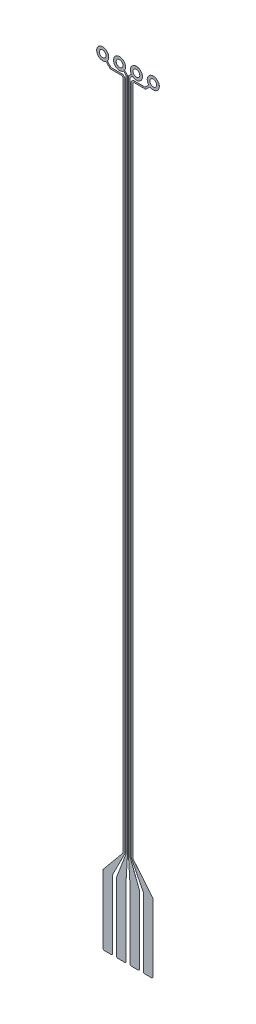
SolidWorks part; units mm, degrees
ref_plane "Front Plane" through (0, 0, 0) normal (0, 0, 1) x (1, 0, 0)
ref_plane "Top Plane" through (0, 0, 0) normal (0, 1, 0) x (1, 0, 0)
ref_plane "Right Plane" through (0, 0, 0) normal (1, 0, 0) x (0, 0, -1)
sketch "Model" plane through (0, 0, 0) normal (0, 0, 1) x (1, 0, 0)
  line L0 (-0.925, -28.446) -> (-0.9247, -28.451)
  line L1 (-0.9247, -28.451) -> (-0.924, -28.4557)
  line L2 (-0.924, -28.4557) -> (-0.923, -28.4605)
  line L3 (-0.923, -28.4605) -> (-0.9213, -28.4652)
  line L4 (-0.9213, -28.4652) -> (-0.919, -28.4695)
  line L5 (-0.919, -28.4695) -> (-0.9165, -28.4737)
  line L6 (-0.9165, -28.4737) -> (-0.9137, -28.4778)
  line L7 (-0.9137, -28.4778) -> (-0.9105, -28.4815)
  line L8 (-0.9105, -28.4815) -> (-0.9068, -28.4847)
  line L9 (-0.9068, -28.4847) -> (-0.9027, -28.4875)
  line L10 (-0.9027, -28.4875) -> (-0.8985, -28.49)
  line L11 (-0.8985, -28.49) -> (-0.8942, -28.4922)
  line L12 (-0.8942, -28.4922) -> (-0.8895, -28.494)
  line L13 (-0.8895, -28.494) -> (-0.8848, -28.495)
  line L14 (-0.8848, -28.495) -> (-0.88, -28.4958)
  line L15 (-0.88, -28.4958) -> (-0.875, -28.496)
  line L16 (-0.875, -28.496) -> (-0.625, -28.496)
  line L17 (-0.625, -28.496) -> (-0.62, -28.4958)
  line L18 (-0.62, -28.4958) -> (-0.6153, -28.495)
  line L19 (-0.6153, -28.495) -> (-0.6105, -28.494)
  line L20 (-0.6105, -28.494) -> (-0.6057, -28.4922)
  line L21 (-0.6057, -28.4922) -> (-0.6015, -28.49)
  line L22 (-0.6015, -28.49) -> (-0.5973, -28.4875)
  line L23 (-0.5973, -28.4875) -> (-0.5933, -28.4847)
  line L24 (-0.5933, -28.4847) -> (-0.5895, -28.4815)
  line L25 (-0.5895, -28.4815) -> (-0.5862, -28.4778)
  line L26 (-0.5862, -28.4778) -> (-0.5835, -28.4737)
  line L27 (-0.5835, -28.4737) -> (-0.581, -28.4695)
  line L28 (-0.581, -28.4695) -> (-0.5787, -28.4652)
  line L29 (-0.5787, -28.4652) -> (-0.577, -28.4605)
  line L30 (-0.577, -28.4605) -> (-0.576, -28.4557)
  line L31 (-0.576, -28.4557) -> (-0.5753, -28.451)
  line L32 (-0.5753, -28.451) -> (-0.575, -28.446)
  line L33 (-0.575, -28.446) -> (-0.575, -25.896)
  line L34 (-0.575, -25.896) -> (-0.12, -24.996)
  line L35 (-0.12, -24.996) -> (-0.12, 0.0424)
  line L36 (-0.18, 0.0176) -> (-0.18, -24.996)
  line L37 (-0.02, -24.996) -> (-0.02, 0.1724)
  line L38 (-0.18, -24.996) -> (-0.925, -25.896)
  line L39 (-0.925, -25.896) -> (-0.925, -28.446)
  line L40 (-0.425, -28.446) -> (-0.4248, -28.451)
  line L41 (-0.4248, -28.451) -> (-0.424, -28.4557)
  line L42 (-0.424, -28.4557) -> (-0.423, -28.4605)
  line L43 (-0.423, -28.4605) -> (-0.4212, -28.4652)
  line L44 (-0.4212, -28.4652) -> (-0.419, -28.4695)
  line L45 (-0.419, -28.4695) -> (-0.4165, -28.4737)
  line L46 (-0.4165, -28.4737) -> (-0.4138, -28.4778)
  line L47 (-0.4138, -28.4778) -> (-0.4105, -28.4815)
  line L48 (-0.4105, -28.4815) -> (-0.4068, -28.4847)
  line L49 (-0.4068, -28.4847) -> (-0.4027, -28.4875)
  line L50 (-0.4027, -28.4875) -> (-0.3985, -28.49)
  line L51 (-0.3985, -28.49) -> (-0.3942, -28.4922)
  line L52 (-0.3942, -28.4922) -> (-0.3895, -28.494)
  line L53 (-0.3895, -28.494) -> (-0.3847, -28.495)
  line L54 (-0.3847, -28.495) -> (-0.38, -28.4958)
  line L55 (-0.38, -28.4958) -> (-0.375, -28.496)
  line L56 (-0.375, -28.496) -> (-0.125, -28.496)
  line L57 (-0.125, -28.496) -> (-0.12, -28.4958)
  line L58 (-0.12, -28.4958) -> (-0.1152, -28.495)
  line L59 (-0.1152, -28.495) -> (-0.1105, -28.494)
  line L60 (-0.1105, -28.494) -> (-0.1057, -28.4922)
  line L61 (-0.1057, -28.4922) -> (-0.1015, -28.49)
  line L62 (-0.1015, -28.49) -> (-0.0972, -28.4875)
  line L63 (-0.0972, -28.4875) -> (-0.0932, -28.4847)
  line L64 (-0.0932, -28.4847) -> (-0.0895, -28.4815)
  line L65 (-0.0895, -28.4815) -> (-0.0862, -28.4778)
  line L66 (-0.0862, -28.4778) -> (-0.0835, -28.4737)
  line L67 (-0.0835, -28.4737) -> (-0.081, -28.4695)
  line L68 (-0.081, -28.4695) -> (-0.0787, -28.4652)
  line L69 (-0.0787, -28.4652) -> (-0.077, -28.4605)
  line L70 (-0.077, -28.4605) -> (-0.076, -28.4557)
  line L71 (-0.076, -28.4557) -> (-0.0752, -28.451)
  line L72 (-0.0752, -28.451) -> (-0.075, -28.446)
  line L73 (-0.075, -28.446) -> (-0.075, -25.896)
  line L74 (-0.075, -25.896) -> (-0.02, -24.996)
  line L75 (-0.08, 0.1476) -> (-0.08, -24.996)
  line L76 (0.08, -24.996) -> (0.08, 0.145)
  line L77 (0.02, 0.1699) -> (0.02, -24.996)
  line L78 (-0.08, -24.996) -> (-0.425, -25.896)
  line L79 (-0.425, -25.896) -> (-0.425, -28.446)
  line L80 (0.02, -24.996) -> (0.075, -25.896)
  line L81 (0.075, -25.896) -> (0.075, -28.446)
  line L82 (0.075, -28.446) -> (0.0752, -28.451)
  line L83 (0.0752, -28.451) -> (0.076, -28.4557)
  line L84 (0.076, -28.4557) -> (0.077, -28.4605)
  line L85 (0.077, -28.4605) -> (0.0787, -28.4652)
  line L86 (0.0787, -28.4652) -> (0.081, -28.4695)
  line L87 (0.081, -28.4695) -> (0.0835, -28.4737)
  line L88 (0.0835, -28.4737) -> (0.0862, -28.4778)
  line L89 (0.0862, -28.4778) -> (0.0895, -28.4815)
  line L90 (0.0895, -28.4815) -> (0.0932, -28.4847)
  line L91 (0.0932, -28.4847) -> (0.0972, -28.4875)
  line L92 (0.0972, -28.4875) -> (0.1015, -28.49)
  line L93 (0.1015, -28.49) -> (0.1057, -28.4922)
  line L94 (0.1057, -28.4922) -> (0.1105, -28.494)
  line L95 (0.1105, -28.494) -> (0.1152, -28.495)
  line L96 (0.1152, -28.495) -> (0.12, -28.4958)
  line L97 (0.12, -28.4958) -> (0.125, -28.496)
  line L98 (0.125, -28.496) -> (0.375, -28.496)
  line L99 (0.375, -28.496) -> (0.38, -28.4958)
  line L100 (0.38, -28.4958) -> (0.3847, -28.495)
  line L101 (0.3847, -28.495) -> (0.3895, -28.494)
  line L102 (0.3895, -28.494) -> (0.3942, -28.4922)
  line L103 (0.3942, -28.4922) -> (0.3985, -28.49)
  line L104 (0.3985, -28.49) -> (0.4027, -28.4875)
  line L105 (0.4027, -28.4875) -> (0.4068, -28.4847)
  line L106 (0.4068, -28.4847) -> (0.4105, -28.4815)
  line L107 (0.4105, -28.4815) -> (0.4138, -28.4778)
  line L108 (0.4138, -28.4778) -> (0.4165, -28.4737)
  line L109 (0.4165, -28.4737) -> (0.419, -28.4695)
  line L110 (0.419, -28.4695) -> (0.4212, -28.4652)
  line L111 (0.4212, -28.4652) -> (0.423, -28.4605)
  line L112 (0.423, -28.4605) -> (0.424, -28.4557)
  line L113 (0.424, -28.4557) -> (0.4248, -28.451)
  line L114 (0.4248, -28.451) -> (0.425, -28.446)
  line L115 (0.425, -28.446) -> (0.425, -25.896)
  line L116 (0.425, -25.896) -> (0.08, -24.996)
  line L117 (0.18, -24.996) -> (0.18, 0.015)
  line L118 (0.12, 0.0399) -> (0.12, -24.996)
  line L120 (0.12, -24.996) -> (0.575, -25.896)
  line L121 (0.575, -25.896) -> (0.575, -28.446)
  line L122 (0.575, -28.446) -> (0.5753, -28.451)
  line L123 (0.5753, -28.451) -> (0.576, -28.4557)
  line L124 (0.576, -28.4557) -> (0.577, -28.4605)
  line L125 (0.577, -28.4605) -> (0.5787, -28.4652)
  line L126 (0.5787, -28.4652) -> (0.581, -28.4695)
  line L127 (0.581, -28.4695) -> (0.5835, -28.4737)
  line L128 (0.5835, -28.4737) -> (0.5862, -28.4778)
  line L129 (0.5862, -28.4778) -> (0.5895, -28.4815)
  line L130 (0.5895, -28.4815) -> (0.5933, -28.4847)
  line L131 (0.5933, -28.4847) -> (0.5973, -28.4875)
  line L132 (0.5973, -28.4875) -> (0.6015, -28.49)
  line L133 (0.6015, -28.49) -> (0.6057, -28.4922)
  line L134 (0.6057, -28.4922) -> (0.6105, -28.494)
  line L135 (0.6105, -28.494) -> (0.6153, -28.495)
  line L136 (0.6153, -28.495) -> (0.62, -28.4958)
  line L137 (0.62, -28.4958) -> (0.625, -28.496)
  line L138 (0.625, -28.496) -> (0.875, -28.496)
  line L139 (0.875, -28.496) -> (0.88, -28.4958)
  line L140 (0.88, -28.4958) -> (0.8848, -28.495)
  line L141 (0.8848, -28.495) -> (0.8895, -28.494)
  line L142 (0.8895, -28.494) -> (0.8942, -28.4922)
  line L143 (0.8942, -28.4922) -> (0.8985, -28.49)
  line L144 (0.8985, -28.49) -> (0.9027, -28.4875)
  line L145 (0.9027, -28.4875) -> (0.9068, -28.4847)
  line L146 (0.9068, -28.4847) -> (0.9105, -28.4815)
  line L147 (0.9105, -28.4815) -> (0.9137, -28.4778)
  line L148 (0.9137, -28.4778) -> (0.9165, -28.4737)
  line L149 (0.9165, -28.4737) -> (0.919, -28.4695)
  line L150 (0.919, -28.4695) -> (0.9213, -28.4652)
  line L151 (0.9213, -28.4652) -> (0.923, -28.4605)
  line L152 (0.923, -28.4605) -> (0.924, -28.4557)
  line L153 (0.924, -28.4557) -> (0.9247, -28.451)
  line L154 (0.9247, -28.451) -> (0.925, -28.446)
  line L155 (0.925, -28.446) -> (0.925, -25.896)
  line L156 (0.925, -25.896) -> (0.18, -24.996)
  line L162 (0.18, 0.015) -> (0.22, 0.055)
  line L163 (0.22, 0.055) -> (0.66, 0.055)
  line L164 (0.66, 0.055) -> (0.8176, 0.2126)
  line L165 (0.8176, 0.2126) -> (0.8232, 0.209)
  line L166 (0.8232, 0.209) -> (0.8295, 0.2052)
  line L167 (0.8295, 0.2052) -> (0.8357, 0.2017)
  line L168 (0.8357, 0.2017) -> (0.8425, 0.1982)
  line L169 (0.8425, 0.1982) -> (0.849, 0.1953)
  line L170 (0.849, 0.1953) -> (0.8558, 0.1922)
  line L171 (0.8558, 0.1922) -> (0.8627, 0.1895)
  line L172 (0.8627, 0.1895) -> (0.8698, 0.187)
  line L173 (0.8698, 0.187) -> (0.8765, 0.1847)
  line L174 (0.8765, 0.1847) -> (0.8838, 0.1827)
  line L175 (0.8838, 0.1827) -> (0.8907, 0.181)
  line L176 (0.8907, 0.181) -> (0.898, 0.1795)
  line L177 (0.898, 0.1795) -> (0.9055, 0.178)
  line L178 (0.9055, 0.178) -> (0.9125, 0.177)
  line L179 (0.9125, 0.177) -> (0.9197, 0.1762)
  line L180 (0.9197, 0.1762) -> (0.9272, 0.1755)
  line L181 (0.9272, 0.1755) -> (0.9345, 0.1753)
  line L182 (0.9345, 0.1753) -> (0.942, 0.175)
  line L183 (0.942, 0.175) -> (0.9495, 0.1753)
  line L184 (0.9495, 0.1753) -> (0.9567, 0.1755)
  line L185 (0.9567, 0.1755) -> (0.9642, 0.1762)
  line L186 (0.9642, 0.1762) -> (0.9715, 0.177)
  line L187 (0.9715, 0.177) -> (0.9785, 0.178)
  line L188 (0.9785, 0.178) -> (0.986, 0.1795)
  line L189 (0.986, 0.1795) -> (0.9932, 0.181)
  line L190 (0.9932, 0.181) -> (1.0003, 0.1827)
  line L191 (1.0003, 0.1827) -> (1.0075, 0.1847)
  line L192 (1.0075, 0.1847) -> (1.0142, 0.187)
  line L193 (1.0142, 0.187) -> (1.0212, 0.1895)
  line L194 (1.0212, 0.1895) -> (1.0282, 0.1922)
  line L195 (1.0282, 0.1922) -> (1.035, 0.1953)
  line L196 (1.035, 0.1953) -> (1.0415, 0.1982)
  line L197 (1.0415, 0.1982) -> (1.0482, 0.2017)
  line L198 (1.0482, 0.2017) -> (1.0545, 0.2052)
  line L199 (1.0545, 0.2052) -> (1.0607, 0.209)
  line L200 (1.0607, 0.209) -> (1.067, 0.213)
  line L201 (1.067, 0.213) -> (1.0733, 0.2172)
  line L202 (1.0733, 0.2172) -> (1.0787, 0.2215)
  line L203 (1.0787, 0.2215) -> (1.0845, 0.226)
  line L204 (1.0845, 0.226) -> (1.0902, 0.2308)
  line L205 (1.0902, 0.2308) -> (1.0958, 0.2357)
  line L206 (1.0958, 0.2357) -> (1.1062, 0.2462)
  line L207 (1.1062, 0.2462) -> (1.1113, 0.2517)
  line L208 (1.1113, 0.2517) -> (1.116, 0.2575)
  line L209 (1.116, 0.2575) -> (1.1205, 0.2632)
  line L210 (1.1205, 0.2632) -> (1.1247, 0.2687)
  line L211 (1.1247, 0.2687) -> (1.129, 0.275)
  line L212 (1.129, 0.275) -> (1.133, 0.2812)
  line L213 (1.133, 0.2812) -> (1.1367, 0.2875)
  line L214 (1.1367, 0.2875) -> (1.1402, 0.2938)
  line L215 (1.1402, 0.2938) -> (1.1438, 0.3005)
  line L216 (1.1438, 0.3005) -> (1.1467, 0.307)
  line L217 (1.1467, 0.307) -> (1.1498, 0.3138)
  line L218 (1.1498, 0.3138) -> (1.1525, 0.3207)
  line L219 (1.1525, 0.3207) -> (1.155, 0.3277)
  line L220 (1.155, 0.3277) -> (1.1572, 0.3345)
  line L221 (1.1572, 0.3345) -> (1.1592, 0.3417)
  line L222 (1.1592, 0.3417) -> (1.161, 0.3488)
  line L223 (1.161, 0.3488) -> (1.1625, 0.356)
  line L224 (1.1625, 0.356) -> (1.164, 0.3635)
  line L225 (1.164, 0.3635) -> (1.165, 0.3705)
  line L226 (1.165, 0.3705) -> (1.1657, 0.3777)
  line L227 (1.1657, 0.3777) -> (1.1665, 0.3852)
  line L228 (1.1665, 0.3852) -> (1.1667, 0.3925)
  line L229 (1.1667, 0.3925) -> (1.167, 0.4)
  line L230 (1.167, 0.4) -> (1.1667, 0.4075)
  line L231 (1.1667, 0.4075) -> (1.1665, 0.4147)
  line L232 (1.1665, 0.4147) -> (1.1657, 0.4223)
  line L233 (1.1657, 0.4223) -> (1.165, 0.4295)
  line L234 (1.165, 0.4295) -> (1.164, 0.4365)
  line L235 (1.164, 0.4365) -> (1.1625, 0.444)
  line L236 (1.1625, 0.444) -> (1.161, 0.4512)
  line L237 (1.161, 0.4512) -> (1.1592, 0.4582)
  line L238 (1.1592, 0.4582) -> (1.1572, 0.4655)
  line L239 (1.1572, 0.4655) -> (1.155, 0.4722)
  line L240 (1.155, 0.4722) -> (1.1525, 0.4792)
  line L241 (1.1525, 0.4792) -> (1.1498, 0.4862)
  line L242 (1.1498, 0.4862) -> (1.1467, 0.493)
  line L243 (1.1467, 0.493) -> (1.1438, 0.4995)
  line L244 (1.1438, 0.4995) -> (1.1402, 0.5062)
  line L245 (1.1402, 0.5062) -> (1.1367, 0.5125)
  line L246 (1.1367, 0.5125) -> (1.133, 0.5188)
  line L247 (1.133, 0.5188) -> (1.129, 0.525)
  line L248 (1.129, 0.525) -> (1.1247, 0.5312)
  line L249 (1.1247, 0.5312) -> (1.1205, 0.5368)
  line L250 (1.1205, 0.5368) -> (1.116, 0.5425)
  line L251 (1.116, 0.5425) -> (1.1113, 0.5483)
  line L252 (1.1113, 0.5483) -> (1.1062, 0.5537)
  line L253 (1.1062, 0.5537) -> (1.0958, 0.5642)
  line L254 (1.0958, 0.5642) -> (1.0902, 0.5693)
  line L255 (1.0902, 0.5693) -> (1.0845, 0.574)
  line L256 (1.0845, 0.574) -> (1.0787, 0.5785)
  line L257 (1.0787, 0.5785) -> (1.0733, 0.5827)
  line L258 (1.0733, 0.5827) -> (1.067, 0.587)
  line L259 (1.067, 0.587) -> (1.0607, 0.591)
  line L260 (1.0607, 0.591) -> (1.0545, 0.5948)
  line L261 (1.0545, 0.5948) -> (1.0482, 0.5982)
  line L262 (1.0482, 0.5982) -> (1.0415, 0.6018)
  line L263 (1.0415, 0.6018) -> (1.035, 0.6047)
  line L264 (1.035, 0.6047) -> (1.0282, 0.6078)
  line L265 (1.0282, 0.6078) -> (1.0212, 0.6105)
  line L266 (1.0212, 0.6105) -> (1.0142, 0.613)
  line L267 (1.0142, 0.613) -> (1.0075, 0.6153)
  line L268 (1.0075, 0.6153) -> (1.0003, 0.6172)
  line L269 (1.0003, 0.6172) -> (0.9932, 0.619)
  line L270 (0.9932, 0.619) -> (0.986, 0.6205)
  line L271 (0.986, 0.6205) -> (0.9785, 0.622)
  line L272 (0.9785, 0.622) -> (0.9715, 0.623)
  line L273 (0.9715, 0.623) -> (0.9642, 0.6237)
  line L274 (0.9642, 0.6237) -> (0.9567, 0.6245)
  line L275 (0.9567, 0.6245) -> (0.9495, 0.6248)
  line L276 (0.9495, 0.6248) -> (0.942, 0.625)
  line L277 (0.942, 0.625) -> (0.9345, 0.6248)
  line L278 (0.9345, 0.6248) -> (0.9272, 0.6245)
  line L279 (0.9272, 0.6245) -> (0.9197, 0.6237)
  line L280 (0.9197, 0.6237) -> (0.9125, 0.623)
  line L281 (0.9125, 0.623) -> (0.9055, 0.622)
  line L282 (0.9055, 0.622) -> (0.898, 0.6205)
  line L283 (0.898, 0.6205) -> (0.8907, 0.619)
  line L284 (0.8907, 0.619) -> (0.8838, 0.6172)
  line L285 (0.8838, 0.6172) -> (0.8765, 0.6153)
  line L286 (0.8765, 0.6153) -> (0.8698, 0.613)
  line L287 (0.8698, 0.613) -> (0.8627, 0.6105)
  line L288 (0.8627, 0.6105) -> (0.8558, 0.6078)
  line L289 (0.8558, 0.6078) -> (0.849, 0.6047)
  line L290 (0.849, 0.6047) -> (0.843, 0.602)
  line L292 (0.843, 0.4763) -> (0.8462, 0.4803)
  line L293 (0.8462, 0.4803) -> (0.8497, 0.4842)
  line L294 (0.8497, 0.4842) -> (0.8535, 0.4882)
  line L295 (0.8535, 0.4882) -> (0.8578, 0.4922)
  line L296 (0.8578, 0.4922) -> (0.8618, 0.4957)
  line L297 (0.8618, 0.4957) -> (0.8658, 0.499)
  line L298 (0.8658, 0.499) -> (0.8705, 0.5025)
  line L299 (0.8705, 0.5025) -> (0.875, 0.5055)
  line L300 (0.875, 0.5055) -> (0.8795, 0.5082)
  line L301 (0.8795, 0.5082) -> (0.8842, 0.5108)
  line L302 (0.8842, 0.5108) -> (0.8892, 0.5132)
  line L303 (0.8892, 0.5132) -> (0.8942, 0.5155)
  line L304 (0.8942, 0.5155) -> (0.899, 0.5172)
  line L305 (0.899, 0.5172) -> (0.9042, 0.519)
  line L306 (0.9042, 0.519) -> (0.9097, 0.5207)
  line L307 (0.9097, 0.5207) -> (0.915, 0.522)
  line L308 (0.915, 0.522) -> (0.9202, 0.523)
  line L309 (0.9202, 0.523) -> (0.9255, 0.5238)
  line L310 (0.9255, 0.5238) -> (0.931, 0.5245)
  line L311 (0.931, 0.5245) -> (0.942, 0.525)
  line L312 (0.942, 0.525) -> (0.953, 0.5245)
  line L313 (0.953, 0.5245) -> (0.9585, 0.5238)
  line L314 (0.9585, 0.5238) -> (0.9637, 0.523)
  line L315 (0.9637, 0.523) -> (0.969, 0.522)
  line L316 (0.969, 0.522) -> (0.9742, 0.5207)
  line L317 (0.9742, 0.5207) -> (0.9797, 0.519)
  line L318 (0.9797, 0.519) -> (0.985, 0.5172)
  line L319 (0.985, 0.5172) -> (0.9897, 0.5155)
  line L320 (0.9897, 0.5155) -> (0.9948, 0.5132)
  line L321 (0.9948, 0.5132) -> (0.9998, 0.5108)
  line L322 (0.9998, 0.5108) -> (1.0045, 0.5082)
  line L323 (1.0045, 0.5082) -> (1.009, 0.5055)
  line L324 (1.009, 0.5055) -> (1.0135, 0.5025)
  line L325 (1.0135, 0.5025) -> (1.0183, 0.499)
  line L326 (1.0183, 0.499) -> (1.0222, 0.4957)
  line L327 (1.0222, 0.4957) -> (1.0263, 0.4922)
  line L328 (1.0263, 0.4922) -> (1.0305, 0.4882)
  line L329 (1.0305, 0.4882) -> (1.0343, 0.4842)
  line L330 (1.0343, 0.4842) -> (1.0377, 0.4803)
  line L331 (1.0377, 0.4803) -> (1.041, 0.4763)
  line L332 (1.041, 0.4763) -> (1.0445, 0.4715)
  line L333 (1.0445, 0.4715) -> (1.0475, 0.467)
  line L334 (1.0475, 0.467) -> (1.0502, 0.4625)
  line L335 (1.0502, 0.4625) -> (1.0527, 0.4577)
  line L336 (1.0527, 0.4577) -> (1.0553, 0.4527)
  line L337 (1.0553, 0.4527) -> (1.0575, 0.4477)
  line L338 (1.0575, 0.4477) -> (1.0592, 0.443)
  line L339 (1.0592, 0.443) -> (1.061, 0.4377)
  line L340 (1.061, 0.4377) -> (1.0627, 0.4322)
  line L341 (1.0627, 0.4322) -> (1.064, 0.427)
  line L342 (1.064, 0.427) -> (1.065, 0.4217)
  line L343 (1.065, 0.4217) -> (1.0657, 0.4165)
  line L344 (1.0657, 0.4165) -> (1.0665, 0.411)
  line L345 (1.0665, 0.411) -> (1.067, 0.4)
  line L346 (1.067, 0.4) -> (1.0665, 0.389)
  line L347 (1.0665, 0.389) -> (1.0657, 0.3835)
  line L348 (1.0657, 0.3835) -> (1.065, 0.3783)
  line L349 (1.065, 0.3783) -> (1.064, 0.373)
  line L350 (1.064, 0.373) -> (1.0627, 0.3677)
  line L351 (1.0627, 0.3677) -> (1.061, 0.3623)
  line L352 (1.061, 0.3623) -> (1.0592, 0.357)
  line L353 (1.0592, 0.357) -> (1.0575, 0.3522)
  line L354 (1.0575, 0.3522) -> (1.0553, 0.3473)
  line L355 (1.0553, 0.3473) -> (1.0527, 0.3422)
  line L356 (1.0527, 0.3422) -> (1.0502, 0.3375)
  line L357 (1.0502, 0.3375) -> (1.0475, 0.333)
  line L358 (1.0475, 0.333) -> (1.0445, 0.3285)
  line L359 (1.0445, 0.3285) -> (1.041, 0.3237)
  line L360 (1.041, 0.3237) -> (1.0377, 0.3197)
  line L361 (1.0377, 0.3197) -> (1.0343, 0.3158)
  line L362 (1.0343, 0.3158) -> (1.0305, 0.3117)
  line L363 (1.0305, 0.3117) -> (1.0263, 0.3077)
  line L364 (1.0263, 0.3077) -> (1.0222, 0.3043)
  line L365 (1.0222, 0.3043) -> (1.0183, 0.301)
  line L366 (1.0183, 0.301) -> (1.0135, 0.2975)
  line L367 (1.0135, 0.2975) -> (1.009, 0.2945)
  line L368 (1.009, 0.2945) -> (1.0045, 0.2917)
  line L369 (1.0045, 0.2917) -> (0.9998, 0.2893)
  line L370 (0.9998, 0.2893) -> (0.9948, 0.2868)
  line L371 (0.9948, 0.2868) -> (0.9897, 0.2845)
  line L372 (0.9897, 0.2845) -> (0.985, 0.2827)
  line L373 (0.985, 0.2827) -> (0.9797, 0.281)
  line L374 (0.9797, 0.281) -> (0.9742, 0.2792)
  line L375 (0.9742, 0.2792) -> (0.969, 0.278)
  line L376 (0.969, 0.278) -> (0.9637, 0.277)
  line L377 (0.9637, 0.277) -> (0.9585, 0.2762)
  line L378 (0.9585, 0.2762) -> (0.953, 0.2755)
  line L379 (0.953, 0.2755) -> (0.942, 0.275)
  line L380 (0.942, 0.275) -> (0.931, 0.2755)
  line L381 (0.931, 0.2755) -> (0.9255, 0.2762)
  line L382 (0.9255, 0.2762) -> (0.9202, 0.277)
  line L383 (0.9202, 0.277) -> (0.915, 0.278)
  line L384 (0.915, 0.278) -> (0.9097, 0.2792)
  line L385 (0.9097, 0.2792) -> (0.9042, 0.281)
  line L386 (0.9042, 0.281) -> (0.899, 0.2827)
  line L387 (0.899, 0.2827) -> (0.8942, 0.2845)
  line L388 (0.8942, 0.2845) -> (0.8892, 0.2868)
  line L389 (0.8892, 0.2868) -> (0.8842, 0.2893)
  line L390 (0.8842, 0.2893) -> (0.8795, 0.2917)
  line L391 (0.8795, 0.2917) -> (0.875, 0.2945)
  line L392 (0.875, 0.2945) -> (0.8705, 0.2975)
  line L393 (0.8705, 0.2975) -> (0.8658, 0.301)
  line L394 (0.8658, 0.301) -> (0.8618, 0.3043)
  line L395 (0.8618, 0.3043) -> (0.8578, 0.3077)
  line L396 (0.8578, 0.3077) -> (0.8535, 0.3117)
  line L397 (0.8535, 0.3117) -> (0.8497, 0.3158)
  line L398 (0.8497, 0.3158) -> (0.8462, 0.3197)
  line L399 (0.8462, 0.3197) -> (0.843, 0.3237)
  line L400 (0.843, 0.3237) -> (0.8395, 0.3285)
  line L401 (0.8395, 0.3285) -> (0.8365, 0.333)
  line L402 (0.8365, 0.333) -> (0.8337, 0.3375)
  line L403 (0.8337, 0.3375) -> (0.8312, 0.3422)
  line L404 (0.8312, 0.3422) -> (0.8287, 0.3473)
  line L405 (0.8287, 0.3473) -> (0.8265, 0.3522)
  line L406 (0.8265, 0.3522) -> (0.8247, 0.357)
  line L407 (0.8247, 0.357) -> (0.823, 0.3623)
  line L408 (0.823, 0.3623) -> (0.8212, 0.3677)
  line L409 (0.8212, 0.3677) -> (0.82, 0.373)
  line L410 (0.82, 0.373) -> (0.819, 0.3783)
  line L411 (0.819, 0.3783) -> (0.8182, 0.3835)
  line L412 (0.8182, 0.3835) -> (0.8175, 0.389)
  line L413 (0.8175, 0.389) -> (0.817, 0.4)
  line L414 (0.817, 0.4) -> (0.8175, 0.411)
  line L415 (0.8175, 0.411) -> (0.8182, 0.4165)
  line L416 (0.8182, 0.4165) -> (0.819, 0.4217)
  line L417 (0.819, 0.4217) -> (0.82, 0.427)
  line L418 (0.82, 0.427) -> (0.8212, 0.4322)
  line L419 (0.8212, 0.4322) -> (0.823, 0.4377)
  line L420 (0.823, 0.4377) -> (0.8247, 0.443)
  line L421 (0.8247, 0.443) -> (0.8265, 0.4477)
  line L422 (0.8265, 0.4477) -> (0.8287, 0.4527)
  line L423 (0.8287, 0.4527) -> (0.8312, 0.4577)
  line L424 (0.8312, 0.4577) -> (0.8337, 0.4625)
  line L425 (0.8337, 0.4625) -> (0.8365, 0.467)
  line L426 (0.8365, 0.467) -> (0.8395, 0.4715)
  line L427 (0.8395, 0.4715) -> (0.843, 0.4763)
  line L429 (0.843, 0.602) -> (0.8425, 0.6018)
  line L430 (0.8425, 0.6018) -> (0.8357, 0.5982)
  line L431 (0.8357, 0.5982) -> (0.8295, 0.5948)
  line L432 (0.8295, 0.5948) -> (0.8232, 0.591)
  line L433 (0.8232, 0.591) -> (0.817, 0.587)
  line L434 (0.817, 0.587) -> (0.8107, 0.5827)
  line L435 (0.8107, 0.5827) -> (0.8053, 0.5785)
  line L436 (0.8053, 0.5785) -> (0.7995, 0.574)
  line L437 (0.7995, 0.574) -> (0.7937, 0.5693)
  line L438 (0.7937, 0.5693) -> (0.7883, 0.5642)
  line L439 (0.7883, 0.5642) -> (0.7778, 0.5537)
  line L440 (0.7778, 0.5537) -> (0.7728, 0.5483)
  line L441 (0.7728, 0.5483) -> (0.768, 0.5425)
  line L442 (0.768, 0.5425) -> (0.7635, 0.5368)
  line L443 (0.7635, 0.5368) -> (0.7592, 0.5312)
  line L444 (0.7592, 0.5312) -> (0.755, 0.525)
  line L445 (0.755, 0.525) -> (0.751, 0.5188)
  line L446 (0.751, 0.5188) -> (0.7472, 0.5125)
  line L447 (0.7472, 0.5125) -> (0.7437, 0.5062)
  line L448 (0.7437, 0.5062) -> (0.7402, 0.4995)
  line L449 (0.7402, 0.4995) -> (0.7372, 0.493)
  line L450 (0.7372, 0.493) -> (0.7342, 0.4862)
  line L451 (0.7342, 0.4862) -> (0.7315, 0.4792)
  line L452 (0.7315, 0.4792) -> (0.729, 0.4722)
  line L453 (0.729, 0.4722) -> (0.7268, 0.4655)
  line L454 (0.7268, 0.4655) -> (0.7247, 0.4582)
  line L455 (0.7247, 0.4582) -> (0.723, 0.4512)
  line L456 (0.723, 0.4512) -> (0.7215, 0.444)
  line L457 (0.7215, 0.444) -> (0.72, 0.4365)
  line L458 (0.72, 0.4365) -> (0.719, 0.4295)
  line L459 (0.719, 0.4295) -> (0.7182, 0.4223)
  line L460 (0.7182, 0.4223) -> (0.7175, 0.4147)
  line L461 (0.7175, 0.4147) -> (0.7173, 0.4075)
  line L462 (0.7173, 0.4075) -> (0.717, 0.4)
  line L463 (0.717, 0.4) -> (0.7173, 0.3925)
  line L464 (0.7173, 0.3925) -> (0.7175, 0.3852)
  line L465 (0.7175, 0.3852) -> (0.7182, 0.3777)
  line L466 (0.7182, 0.3777) -> (0.719, 0.3705)
  line L467 (0.719, 0.3705) -> (0.72, 0.3635)
  line L468 (0.72, 0.3635) -> (0.7215, 0.356)
  line L469 (0.7215, 0.356) -> (0.723, 0.3488)
  line L470 (0.723, 0.3488) -> (0.7247, 0.3417)
  line L471 (0.7247, 0.3417) -> (0.7268, 0.3345)
  line L472 (0.7268, 0.3345) -> (0.729, 0.3277)
  line L473 (0.729, 0.3277) -> (0.7315, 0.3207)
  line L474 (0.7315, 0.3207) -> (0.7342, 0.3138)
  line L475 (0.7342, 0.3138) -> (0.7372, 0.307)
  line L476 (0.7372, 0.307) -> (0.7402, 0.3005)
  line L477 (0.7402, 0.3005) -> (0.7437, 0.2938)
  line L478 (0.7437, 0.2938) -> (0.7472, 0.2875)
  line L479 (0.7472, 0.2875) -> (0.751, 0.2812)
  line L480 (0.751, 0.2812) -> (0.755, 0.275)
  line L481 (0.755, 0.275) -> (0.7592, 0.2687)
  line L482 (0.7592, 0.2687) -> (0.7635, 0.2632)
  line L483 (0.7635, 0.2632) -> (0.768, 0.2575)
  line L484 (0.768, 0.2575) -> (0.7724, 0.2522)
  line L485 (0.7724, 0.2522) -> (0.6351, 0.115)
  line L486 (0.6351, 0.115) -> (0.1951, 0.115)
  line L487 (0.1951, 0.115) -> (0.12, 0.0399)
  line L491 (0.08, 0.145) -> (0.1657, 0.2308)
  line L492 (0.1657, 0.2308) -> (0.1715, 0.226)
  line L493 (0.1715, 0.226) -> (0.1772, 0.2215)
  line L494 (0.1772, 0.2215) -> (0.1827, 0.2172)
  line L495 (0.1827, 0.2172) -> (0.189, 0.213)
  line L496 (0.189, 0.213) -> (0.1953, 0.209)
  line L497 (0.1953, 0.209) -> (0.2015, 0.2052)
  line L498 (0.2015, 0.2052) -> (0.2077, 0.2017)
  line L499 (0.2077, 0.2017) -> (0.2145, 0.1982)
  line L500 (0.2145, 0.1982) -> (0.221, 0.1953)
  line L501 (0.221, 0.1953) -> (0.2277, 0.1922)
  line L502 (0.2277, 0.1922) -> (0.2347, 0.1895)
  line L503 (0.2347, 0.1895) -> (0.2417, 0.187)
  line L504 (0.2417, 0.187) -> (0.2485, 0.1847)
  line L505 (0.2485, 0.1847) -> (0.2558, 0.1827)
  line L506 (0.2558, 0.1827) -> (0.2627, 0.181)
  line L507 (0.2627, 0.181) -> (0.27, 0.1795)
  line L508 (0.27, 0.1795) -> (0.2775, 0.178)
  line L509 (0.2775, 0.178) -> (0.2845, 0.177)
  line L510 (0.2845, 0.177) -> (0.2917, 0.1762)
  line L511 (0.2917, 0.1762) -> (0.2992, 0.1755)
  line L512 (0.2992, 0.1755) -> (0.3065, 0.1753)
  line L513 (0.3065, 0.1753) -> (0.314, 0.175)
  line L514 (0.314, 0.175) -> (0.3215, 0.1753)
  line L515 (0.3215, 0.1753) -> (0.3287, 0.1755)
  line L516 (0.3287, 0.1755) -> (0.3362, 0.1762)
  line L517 (0.3362, 0.1762) -> (0.3435, 0.177)
  line L518 (0.3435, 0.177) -> (0.3505, 0.178)
  line L519 (0.3505, 0.178) -> (0.358, 0.1795)
  line L520 (0.358, 0.1795) -> (0.3652, 0.181)
  line L521 (0.3652, 0.181) -> (0.3722, 0.1827)
  line L522 (0.3722, 0.1827) -> (0.3795, 0.1847)
  line L523 (0.3795, 0.1847) -> (0.3862, 0.187)
  line L524 (0.3862, 0.187) -> (0.3932, 0.1895)
  line L525 (0.3932, 0.1895) -> (0.4002, 0.1922)
  line L526 (0.4002, 0.1922) -> (0.407, 0.1953)
  line L527 (0.407, 0.1953) -> (0.4135, 0.1982)
  line L528 (0.4135, 0.1982) -> (0.4203, 0.2017)
  line L529 (0.4203, 0.2017) -> (0.4265, 0.2052)
  line L530 (0.4265, 0.2052) -> (0.4327, 0.209)
  line L531 (0.4327, 0.209) -> (0.439, 0.213)
  line L532 (0.439, 0.213) -> (0.4452, 0.2172)
  line L533 (0.4452, 0.2172) -> (0.4507, 0.2215)
  line L534 (0.4507, 0.2215) -> (0.4565, 0.226)
  line L535 (0.4565, 0.226) -> (0.4622, 0.2308)
  line L536 (0.4622, 0.2308) -> (0.4677, 0.2357)
  line L537 (0.4677, 0.2357) -> (0.4783, 0.2462)
  line L538 (0.4783, 0.2462) -> (0.4832, 0.2517)
  line L539 (0.4832, 0.2517) -> (0.488, 0.2575)
  line L540 (0.488, 0.2575) -> (0.4925, 0.2632)
  line L541 (0.4925, 0.2632) -> (0.4968, 0.2687)
  line L542 (0.4968, 0.2687) -> (0.501, 0.275)
  line L543 (0.501, 0.275) -> (0.505, 0.2812)
  line L544 (0.505, 0.2812) -> (0.5087, 0.2875)
  line L545 (0.5087, 0.2875) -> (0.5122, 0.2938)
  line L546 (0.5122, 0.2938) -> (0.5157, 0.3005)
  line L547 (0.5157, 0.3005) -> (0.5188, 0.307)
  line L548 (0.5188, 0.307) -> (0.5217, 0.3138)
  line L549 (0.5217, 0.3138) -> (0.5245, 0.3207)
  line L550 (0.5245, 0.3207) -> (0.527, 0.3277)
  line L551 (0.527, 0.3277) -> (0.5292, 0.3345)
  line L552 (0.5292, 0.3345) -> (0.5312, 0.3417)
  line L553 (0.5312, 0.3417) -> (0.533, 0.3488)
  line L554 (0.533, 0.3488) -> (0.5345, 0.356)
  line L555 (0.5345, 0.356) -> (0.536, 0.3635)
  line L556 (0.536, 0.3635) -> (0.537, 0.3705)
  line L557 (0.537, 0.3705) -> (0.5377, 0.3777)
  line L558 (0.5377, 0.3777) -> (0.5385, 0.3852)
  line L559 (0.5385, 0.3852) -> (0.5387, 0.3925)
  line L560 (0.5387, 0.3925) -> (0.539, 0.4)
  line L561 (0.539, 0.4) -> (0.5387, 0.4075)
  line L562 (0.5387, 0.4075) -> (0.5385, 0.4147)
  line L563 (0.5385, 0.4147) -> (0.5377, 0.4223)
  line L564 (0.5377, 0.4223) -> (0.537, 0.4295)
  line L565 (0.537, 0.4295) -> (0.536, 0.4365)
  line L566 (0.536, 0.4365) -> (0.5345, 0.444)
  line L567 (0.5345, 0.444) -> (0.533, 0.4512)
  line L568 (0.533, 0.4512) -> (0.5312, 0.4582)
  line L569 (0.5312, 0.4582) -> (0.5292, 0.4655)
  line L570 (0.5292, 0.4655) -> (0.527, 0.4722)
  line L571 (0.527, 0.4722) -> (0.5245, 0.4792)
  line L572 (0.5245, 0.4792) -> (0.5217, 0.4862)
  line L573 (0.5217, 0.4862) -> (0.5188, 0.493)
  line L574 (0.5188, 0.493) -> (0.5157, 0.4995)
  line L575 (0.5157, 0.4995) -> (0.5122, 0.5062)
  line L576 (0.5122, 0.5062) -> (0.5087, 0.5125)
  line L577 (0.5087, 0.5125) -> (0.505, 0.5188)
  line L578 (0.505, 0.5188) -> (0.501, 0.525)
  line L579 (0.501, 0.525) -> (0.4968, 0.5312)
  line L580 (0.4968, 0.5312) -> (0.4925, 0.5368)
  line L581 (0.4925, 0.5368) -> (0.488, 0.5425)
  line L582 (0.488, 0.5425) -> (0.4832, 0.5483)
  line L583 (0.4832, 0.5483) -> (0.4783, 0.5537)
  line L584 (0.4783, 0.5537) -> (0.4677, 0.5642)
  line L585 (0.4677, 0.5642) -> (0.4622, 0.5693)
  line L586 (0.4622, 0.5693) -> (0.4565, 0.574)
  line L587 (0.4565, 0.574) -> (0.4507, 0.5785)
  line L588 (0.4507, 0.5785) -> (0.4452, 0.5827)
  line L589 (0.4452, 0.5827) -> (0.439, 0.587)
  line L590 (0.439, 0.587) -> (0.4327, 0.591)
  line L591 (0.4327, 0.591) -> (0.4265, 0.5948)
  line L592 (0.4265, 0.5948) -> (0.4203, 0.5982)
  line L593 (0.4203, 0.5982) -> (0.4135, 0.6018)
  line L594 (0.4135, 0.6018) -> (0.407, 0.6047)
  line L595 (0.407, 0.6047) -> (0.4002, 0.6078)
  line L596 (0.4002, 0.6078) -> (0.3932, 0.6105)
  line L597 (0.3932, 0.6105) -> (0.3862, 0.613)
  line L598 (0.3862, 0.613) -> (0.3795, 0.6153)
  line L599 (0.3795, 0.6153) -> (0.3722, 0.6172)
  line L600 (0.3722, 0.6172) -> (0.3652, 0.619)
  line L601 (0.3652, 0.619) -> (0.358, 0.6205)
  line L602 (0.358, 0.6205) -> (0.3505, 0.622)
  line L603 (0.3505, 0.622) -> (0.3435, 0.623)
  line L604 (0.3435, 0.623) -> (0.3362, 0.6237)
  line L605 (0.3362, 0.6237) -> (0.3287, 0.6245)
  line L606 (0.3287, 0.6245) -> (0.3215, 0.6248)
  line L607 (0.3215, 0.6248) -> (0.314, 0.625)
  line L608 (0.314, 0.625) -> (0.3065, 0.6248)
  line L609 (0.3065, 0.6248) -> (0.2992, 0.6245)
  line L610 (0.2992, 0.6245) -> (0.2917, 0.6237)
  line L611 (0.2917, 0.6237) -> (0.2845, 0.623)
  line L612 (0.2845, 0.623) -> (0.2775, 0.622)
  line L613 (0.2775, 0.622) -> (0.27, 0.6205)
  line L614 (0.27, 0.6205) -> (0.2627, 0.619)
  line L615 (0.2627, 0.619) -> (0.2558, 0.6172)
  line L616 (0.2558, 0.6172) -> (0.2485, 0.6153)
  line L617 (0.2485, 0.6153) -> (0.2417, 0.613)
  line L618 (0.2417, 0.613) -> (0.2347, 0.6105)
  line L619 (0.2347, 0.6105) -> (0.2277, 0.6078)
  line L620 (0.2277, 0.6078) -> (0.221, 0.6047)
  line L621 (0.221, 0.6047) -> (0.2145, 0.6018)
  line L622 (0.2145, 0.6018) -> (0.2077, 0.5982)
  line L623 (0.2077, 0.5982) -> (0.2015, 0.5948)
  line L624 (0.2015, 0.5948) -> (0.1953, 0.591)
  line L625 (0.1953, 0.591) -> (0.1895, 0.5873)
  line L627 (0.1895, 0.411) -> (0.1903, 0.4165)
  line L628 (0.1903, 0.4165) -> (0.191, 0.4217)
  line L629 (0.191, 0.4217) -> (0.192, 0.427)
  line L630 (0.192, 0.427) -> (0.1932, 0.4322)
  line L631 (0.1932, 0.4322) -> (0.195, 0.4377)
  line L632 (0.195, 0.4377) -> (0.1967, 0.443)
  line L633 (0.1967, 0.443) -> (0.1985, 0.4477)
  line L634 (0.1985, 0.4477) -> (0.2008, 0.4527)
  line L635 (0.2008, 0.4527) -> (0.2032, 0.4577)
  line L636 (0.2032, 0.4577) -> (0.2057, 0.4625)
  line L637 (0.2057, 0.4625) -> (0.2085, 0.467)
  line L638 (0.2085, 0.467) -> (0.2115, 0.4715)
  line L639 (0.2115, 0.4715) -> (0.215, 0.4763)
  line L640 (0.215, 0.4763) -> (0.2182, 0.4803)
  line L641 (0.2182, 0.4803) -> (0.2218, 0.4842)
  line L642 (0.2218, 0.4842) -> (0.2255, 0.4882)
  line L643 (0.2255, 0.4882) -> (0.2298, 0.4922)
  line L644 (0.2298, 0.4922) -> (0.2337, 0.4957)
  line L645 (0.2337, 0.4957) -> (0.2377, 0.499)
  line L646 (0.2377, 0.499) -> (0.2425, 0.5025)
  line L647 (0.2425, 0.5025) -> (0.247, 0.5055)
  line L648 (0.247, 0.5055) -> (0.2515, 0.5082)
  line L649 (0.2515, 0.5082) -> (0.2562, 0.5108)
  line L650 (0.2562, 0.5108) -> (0.2612, 0.5132)
  line L651 (0.2612, 0.5132) -> (0.2662, 0.5155)
  line L652 (0.2662, 0.5155) -> (0.271, 0.5172)
  line L653 (0.271, 0.5172) -> (0.2762, 0.519)
  line L654 (0.2762, 0.519) -> (0.2818, 0.5207)
  line L655 (0.2818, 0.5207) -> (0.287, 0.522)
  line L656 (0.287, 0.522) -> (0.2922, 0.523)
  line L657 (0.2922, 0.523) -> (0.2975, 0.5238)
  line L658 (0.2975, 0.5238) -> (0.303, 0.5245)
  line L659 (0.303, 0.5245) -> (0.314, 0.525)
  line L660 (0.314, 0.525) -> (0.325, 0.5245)
  line L661 (0.325, 0.5245) -> (0.3305, 0.5238)
  line L662 (0.3305, 0.5238) -> (0.3357, 0.523)
  line L663 (0.3357, 0.523) -> (0.341, 0.522)
  line L664 (0.341, 0.522) -> (0.3463, 0.5207)
  line L665 (0.3463, 0.5207) -> (0.3517, 0.519)
  line L666 (0.3517, 0.519) -> (0.357, 0.5172)
  line L667 (0.357, 0.5172) -> (0.3617, 0.5155)
  line L668 (0.3617, 0.5155) -> (0.3668, 0.5132)
  line L669 (0.3668, 0.5132) -> (0.3718, 0.5108)
  line L670 (0.3718, 0.5108) -> (0.3765, 0.5082)
  line L671 (0.3765, 0.5082) -> (0.381, 0.5055)
  line L672 (0.381, 0.5055) -> (0.3855, 0.5025)
  line L673 (0.3855, 0.5025) -> (0.3902, 0.499)
  line L674 (0.3902, 0.499) -> (0.3942, 0.4957)
  line L675 (0.3942, 0.4957) -> (0.3982, 0.4922)
  line L676 (0.3982, 0.4922) -> (0.4025, 0.4882)
  line L677 (0.4025, 0.4882) -> (0.4062, 0.4842)
  line L678 (0.4062, 0.4842) -> (0.4097, 0.4803)
  line L679 (0.4097, 0.4803) -> (0.413, 0.4763)
  line L680 (0.413, 0.4763) -> (0.4165, 0.4715)
  line L681 (0.4165, 0.4715) -> (0.4195, 0.467)
  line L682 (0.4195, 0.467) -> (0.4223, 0.4625)
  line L683 (0.4223, 0.4625) -> (0.4248, 0.4577)
  line L684 (0.4248, 0.4577) -> (0.4273, 0.4527)
  line L685 (0.4273, 0.4527) -> (0.4295, 0.4477)
  line L686 (0.4295, 0.4477) -> (0.4312, 0.443)
  line L687 (0.4312, 0.443) -> (0.433, 0.4377)
  line L688 (0.433, 0.4377) -> (0.4347, 0.4322)
  line L689 (0.4347, 0.4322) -> (0.436, 0.427)
  line L690 (0.436, 0.427) -> (0.437, 0.4217)
  line L691 (0.437, 0.4217) -> (0.4377, 0.4165)
  line L692 (0.4377, 0.4165) -> (0.4385, 0.411)
  line L693 (0.4385, 0.411) -> (0.439, 0.4)
  line L694 (0.439, 0.4) -> (0.4385, 0.389)
  line L695 (0.4385, 0.389) -> (0.4377, 0.3835)
  line L696 (0.4377, 0.3835) -> (0.437, 0.3783)
  line L697 (0.437, 0.3783) -> (0.436, 0.373)
  line L698 (0.436, 0.373) -> (0.4347, 0.3677)
  line L699 (0.4347, 0.3677) -> (0.433, 0.3623)
  line L700 (0.433, 0.3623) -> (0.4312, 0.357)
  line L701 (0.4312, 0.357) -> (0.4295, 0.3522)
  line L702 (0.4295, 0.3522) -> (0.4273, 0.3473)
  line L703 (0.4273, 0.3473) -> (0.4248, 0.3422)
  line L704 (0.4248, 0.3422) -> (0.4223, 0.3375)
  line L705 (0.4223, 0.3375) -> (0.4195, 0.333)
  line L706 (0.4195, 0.333) -> (0.4165, 0.3285)
  line L707 (0.4165, 0.3285) -> (0.413, 0.3237)
  line L708 (0.413, 0.3237) -> (0.4097, 0.3197)
  line L709 (0.4097, 0.3197) -> (0.4062, 0.3158)
  line L710 (0.4062, 0.3158) -> (0.4025, 0.3117)
  line L711 (0.4025, 0.3117) -> (0.3982, 0.3077)
  line L712 (0.3982, 0.3077) -> (0.3942, 0.3043)
  line L713 (0.3942, 0.3043) -> (0.3902, 0.301)
  line L714 (0.3902, 0.301) -> (0.3855, 0.2975)
  line L715 (0.3855, 0.2975) -> (0.381, 0.2945)
  line L716 (0.381, 0.2945) -> (0.3765, 0.2917)
  line L717 (0.3765, 0.2917) -> (0.3718, 0.2893)
  line L718 (0.3718, 0.2893) -> (0.3668, 0.2868)
  line L719 (0.3668, 0.2868) -> (0.3617, 0.2845)
  line L720 (0.3617, 0.2845) -> (0.357, 0.2827)
  line L721 (0.357, 0.2827) -> (0.3517, 0.281)
  line L722 (0.3517, 0.281) -> (0.3463, 0.2792)
  line L723 (0.3463, 0.2792) -> (0.341, 0.278)
  line L724 (0.341, 0.278) -> (0.3357, 0.277)
  line L725 (0.3357, 0.277) -> (0.3305, 0.2762)
  line L726 (0.3305, 0.2762) -> (0.325, 0.2755)
  line L727 (0.325, 0.2755) -> (0.314, 0.275)
  line L728 (0.314, 0.275) -> (0.303, 0.2755)
  line L729 (0.303, 0.2755) -> (0.2975, 0.2762)
  line L730 (0.2975, 0.2762) -> (0.2922, 0.277)
  line L731 (0.2922, 0.277) -> (0.287, 0.278)
  line L732 (0.287, 0.278) -> (0.2818, 0.2792)
  line L733 (0.2818, 0.2792) -> (0.2762, 0.281)
  line L734 (0.2762, 0.281) -> (0.271, 0.2827)
  line L735 (0.271, 0.2827) -> (0.2662, 0.2845)
  line L736 (0.2662, 0.2845) -> (0.2612, 0.2868)
  line L737 (0.2612, 0.2868) -> (0.2562, 0.2893)
  line L738 (0.2562, 0.2893) -> (0.2515, 0.2917)
  line L739 (0.2515, 0.2917) -> (0.247, 0.2945)
  line L740 (0.247, 0.2945) -> (0.2425, 0.2975)
  line L741 (0.2425, 0.2975) -> (0.2377, 0.301)
  line L742 (0.2377, 0.301) -> (0.2337, 0.3043)
  line L743 (0.2337, 0.3043) -> (0.2298, 0.3077)
  line L744 (0.2298, 0.3077) -> (0.2255, 0.3117)
  line L745 (0.2255, 0.3117) -> (0.2218, 0.3158)
  line L746 (0.2218, 0.3158) -> (0.2182, 0.3197)
  line L747 (0.2182, 0.3197) -> (0.215, 0.3237)
  line L748 (0.215, 0.3237) -> (0.2115, 0.3285)
  line L749 (0.2115, 0.3285) -> (0.2085, 0.333)
  line L750 (0.2085, 0.333) -> (0.2057, 0.3375)
  line L751 (0.2057, 0.3375) -> (0.2032, 0.3422)
  line L752 (0.2032, 0.3422) -> (0.2008, 0.3473)
  line L753 (0.2008, 0.3473) -> (0.1985, 0.3522)
  line L754 (0.1985, 0.3522) -> (0.1967, 0.357)
  line L755 (0.1967, 0.357) -> (0.195, 0.3623)
  line L756 (0.195, 0.3623) -> (0.1932, 0.3677)
  line L757 (0.1932, 0.3677) -> (0.192, 0.373)
  line L758 (0.192, 0.373) -> (0.191, 0.3783)
  line L759 (0.191, 0.3783) -> (0.1903, 0.3835)
  line L760 (0.1903, 0.3835) -> (0.1895, 0.389)
  line L761 (0.1895, 0.389) -> (0.189, 0.4)
  line L762 (0.189, 0.4) -> (0.1895, 0.411)
  line L764 (0.1895, 0.5873) -> (0.189, 0.587)
  line L765 (0.189, 0.587) -> (0.1827, 0.5827)
  line L766 (0.1827, 0.5827) -> (0.1772, 0.5785)
  line L767 (0.1772, 0.5785) -> (0.1715, 0.574)
  line L768 (0.1715, 0.574) -> (0.1657, 0.5693)
  line L769 (0.1657, 0.5693) -> (0.1603, 0.5642)
  line L770 (0.1603, 0.5642) -> (0.1497, 0.5537)
  line L771 (0.1497, 0.5537) -> (0.1447, 0.5483)
  line L772 (0.1447, 0.5483) -> (0.14, 0.5425)
  line L773 (0.14, 0.5425) -> (0.1355, 0.5368)
  line L774 (0.1355, 0.5368) -> (0.1313, 0.5312)
  line L775 (0.1313, 0.5312) -> (0.127, 0.525)
  line L776 (0.127, 0.525) -> (0.123, 0.5188)
  line L777 (0.123, 0.5188) -> (0.1192, 0.5125)
  line L778 (0.1192, 0.5125) -> (0.1157, 0.5062)
  line L779 (0.1157, 0.5062) -> (0.1122, 0.4995)
  line L780 (0.1122, 0.4995) -> (0.1092, 0.493)
  line L781 (0.1092, 0.493) -> (0.1062, 0.4862)
  line L782 (0.1062, 0.4862) -> (0.1035, 0.4792)
  line L783 (0.1035, 0.4792) -> (0.101, 0.4722)
  line L784 (0.101, 0.4722) -> (0.0988, 0.4655)
  line L785 (0.0988, 0.4655) -> (0.0967, 0.4582)
  line L786 (0.0967, 0.4582) -> (0.095, 0.4512)
  line L787 (0.095, 0.4512) -> (0.0935, 0.444)
  line L788 (0.0935, 0.444) -> (0.092, 0.4365)
  line L789 (0.092, 0.4365) -> (0.091, 0.4295)
  line L790 (0.091, 0.4295) -> (0.0902, 0.4223)
  line L791 (0.0902, 0.4223) -> (0.0895, 0.4147)
  line L792 (0.0895, 0.4147) -> (0.0892, 0.4075)
  line L793 (0.0892, 0.4075) -> (0.089, 0.4)
  line L794 (0.089, 0.4) -> (0.0892, 0.3925)
  line L795 (0.0892, 0.3925) -> (0.0895, 0.3852)
  line L796 (0.0895, 0.3852) -> (0.0902, 0.3777)
  line L797 (0.0902, 0.3777) -> (0.091, 0.3705)
  line L798 (0.091, 0.3705) -> (0.092, 0.3635)
  line L799 (0.092, 0.3635) -> (0.0935, 0.356)
  line L800 (0.0935, 0.356) -> (0.095, 0.3488)
  line L801 (0.095, 0.3488) -> (0.0967, 0.3417)
  line L802 (0.0967, 0.3417) -> (0.0988, 0.3345)
  line L803 (0.0988, 0.3345) -> (0.101, 0.3277)
  line L804 (0.101, 0.3277) -> (0.1035, 0.3207)
  line L805 (0.1035, 0.3207) -> (0.1062, 0.3138)
  line L806 (0.1062, 0.3138) -> (0.1092, 0.307)
  line L807 (0.1092, 0.307) -> (0.1122, 0.3005)
  line L808 (0.1122, 0.3005) -> (0.1157, 0.2938)
  line L809 (0.1157, 0.2938) -> (0.1192, 0.2875)
  line L810 (0.1192, 0.2875) -> (0.123, 0.2812)
  line L811 (0.123, 0.2812) -> (0.1263, 0.2761)
  line L812 (0.1263, 0.2761) -> (0.02, 0.1699)
  line L814 (-0.539, 0.4) -> (-0.5387, 0.3925)
  line L815 (-0.5387, 0.3925) -> (-0.5385, 0.3852)
  line L816 (-0.5385, 0.3852) -> (-0.5377, 0.3777)
  line L817 (-0.5377, 0.3777) -> (-0.537, 0.3705)
  line L818 (-0.537, 0.3705) -> (-0.536, 0.3635)
  line L819 (-0.536, 0.3635) -> (-0.5345, 0.356)
  line L820 (-0.5345, 0.356) -> (-0.533, 0.3488)
  line L821 (-0.533, 0.3488) -> (-0.5312, 0.3417)
  line L822 (-0.5312, 0.3417) -> (-0.5292, 0.3345)
  line L823 (-0.5292, 0.3345) -> (-0.527, 0.3277)
  line L824 (-0.527, 0.3277) -> (-0.5245, 0.3207)
  line L825 (-0.5245, 0.3207) -> (-0.5217, 0.3138)
  line L826 (-0.5217, 0.3138) -> (-0.5188, 0.307)
  line L827 (-0.5188, 0.307) -> (-0.5157, 0.3005)
  line L828 (-0.5157, 0.3005) -> (-0.5122, 0.2938)
  line L829 (-0.5122, 0.2938) -> (-0.5087, 0.2875)
  line L830 (-0.5087, 0.2875) -> (-0.505, 0.2812)
  line L831 (-0.505, 0.2812) -> (-0.501, 0.275)
  line L832 (-0.501, 0.275) -> (-0.4968, 0.2687)
  line L833 (-0.4968, 0.2687) -> (-0.4925, 0.2632)
  line L834 (-0.4925, 0.2632) -> (-0.488, 0.2575)
  line L835 (-0.488, 0.2575) -> (-0.4832, 0.2517)
  line L836 (-0.4832, 0.2517) -> (-0.4783, 0.2462)
  line L837 (-0.4783, 0.2462) -> (-0.4677, 0.2357)
  line L838 (-0.4677, 0.2357) -> (-0.4622, 0.2308)
  line L839 (-0.4622, 0.2308) -> (-0.4565, 0.226)
  line L840 (-0.4565, 0.226) -> (-0.4507, 0.2215)
  line L841 (-0.4507, 0.2215) -> (-0.4452, 0.2172)
  line L842 (-0.4452, 0.2172) -> (-0.439, 0.213)
  line L843 (-0.439, 0.213) -> (-0.4327, 0.209)
  line L844 (-0.4327, 0.209) -> (-0.4265, 0.2052)
  line L845 (-0.4265, 0.2052) -> (-0.4203, 0.2017)
  line L846 (-0.4203, 0.2017) -> (-0.4135, 0.1982)
  line L847 (-0.4135, 0.1982) -> (-0.407, 0.1953)
  line L848 (-0.407, 0.1953) -> (-0.4002, 0.1922)
  line L849 (-0.4002, 0.1922) -> (-0.3932, 0.1895)
  line L850 (-0.3932, 0.1895) -> (-0.3862, 0.187)
  line L851 (-0.3862, 0.187) -> (-0.3795, 0.1847)
  line L852 (-0.3795, 0.1847) -> (-0.3722, 0.1827)
  line L853 (-0.3722, 0.1827) -> (-0.3652, 0.181)
  line L854 (-0.3652, 0.181) -> (-0.358, 0.1795)
  line L855 (-0.358, 0.1795) -> (-0.3505, 0.178)
  line L856 (-0.3505, 0.178) -> (-0.3435, 0.177)
  line L857 (-0.3435, 0.177) -> (-0.3362, 0.1762)
  line L858 (-0.3362, 0.1762) -> (-0.3287, 0.1755)
  line L859 (-0.3287, 0.1755) -> (-0.3215, 0.1753)
  line L860 (-0.3215, 0.1753) -> (-0.314, 0.175)
  line L861 (-0.314, 0.175) -> (-0.3065, 0.1753)
  line L862 (-0.3065, 0.1753) -> (-0.2992, 0.1755)
  line L863 (-0.2992, 0.1755) -> (-0.2917, 0.1762)
  line L864 (-0.2917, 0.1762) -> (-0.2845, 0.177)
  line L865 (-0.2845, 0.177) -> (-0.2775, 0.178)
  line L866 (-0.2775, 0.178) -> (-0.27, 0.1795)
  line L867 (-0.27, 0.1795) -> (-0.2627, 0.181)
  line L868 (-0.2627, 0.181) -> (-0.2558, 0.1827)
  line L869 (-0.2558, 0.1827) -> (-0.2485, 0.1847)
  line L870 (-0.2485, 0.1847) -> (-0.2417, 0.187)
  line L871 (-0.2417, 0.187) -> (-0.2347, 0.1895)
  line L872 (-0.2347, 0.1895) -> (-0.2277, 0.1922)
  line L873 (-0.2277, 0.1922) -> (-0.221, 0.1953)
  line L874 (-0.221, 0.1953) -> (-0.2145, 0.1982)
  line L875 (-0.2145, 0.1982) -> (-0.2077, 0.2017)
  line L876 (-0.2077, 0.2017) -> (-0.2015, 0.2052)
  line L877 (-0.2015, 0.2052) -> (-0.1953, 0.209)
  line L878 (-0.1953, 0.209) -> (-0.189, 0.213)
  line L879 (-0.189, 0.213) -> (-0.1827, 0.2172)
  line L880 (-0.1827, 0.2172) -> (-0.1772, 0.2215)
  line L881 (-0.1772, 0.2215) -> (-0.1715, 0.226)
  line L882 (-0.1715, 0.226) -> (-0.1657, 0.2308)
  line L883 (-0.1657, 0.2308) -> (-0.1644, 0.232)
  line L884 (-0.1644, 0.232) -> (-0.08, 0.1476)
  line L888 (-0.02, 0.1724) -> (-0.1253, 0.2777)
  line L889 (-0.1253, 0.2777) -> (-0.123, 0.2812)
  line L890 (-0.123, 0.2812) -> (-0.1192, 0.2875)
  line L891 (-0.1192, 0.2875) -> (-0.1157, 0.2938)
  line L892 (-0.1157, 0.2938) -> (-0.1122, 0.3005)
  line L893 (-0.1122, 0.3005) -> (-0.1092, 0.307)
  line L894 (-0.1092, 0.307) -> (-0.1062, 0.3138)
  line L895 (-0.1062, 0.3138) -> (-0.1035, 0.3207)
  line L896 (-0.1035, 0.3207) -> (-0.101, 0.3277)
  line L897 (-0.101, 0.3277) -> (-0.0988, 0.3345)
  line L898 (-0.0988, 0.3345) -> (-0.0967, 0.3417)
  line L899 (-0.0967, 0.3417) -> (-0.095, 0.3488)
  line L900 (-0.095, 0.3488) -> (-0.0935, 0.356)
  line L901 (-0.0935, 0.356) -> (-0.092, 0.3635)
  line L902 (-0.092, 0.3635) -> (-0.091, 0.3705)
  line L903 (-0.091, 0.3705) -> (-0.0902, 0.3777)
  line L904 (-0.0902, 0.3777) -> (-0.0895, 0.3852)
  line L905 (-0.0895, 0.3852) -> (-0.0892, 0.3925)
  line L906 (-0.0892, 0.3925) -> (-0.089, 0.4)
  line L907 (-0.089, 0.4) -> (-0.0892, 0.4075)
  line L908 (-0.0892, 0.4075) -> (-0.0895, 0.4147)
  line L909 (-0.0895, 0.4147) -> (-0.0902, 0.4223)
  line L910 (-0.0902, 0.4223) -> (-0.091, 0.4295)
  line L911 (-0.091, 0.4295) -> (-0.092, 0.4365)
  line L912 (-0.092, 0.4365) -> (-0.0935, 0.444)
  line L913 (-0.0935, 0.444) -> (-0.095, 0.4512)
  line L914 (-0.095, 0.4512) -> (-0.0967, 0.4582)
  line L915 (-0.0967, 0.4582) -> (-0.0988, 0.4655)
  line L916 (-0.0988, 0.4655) -> (-0.101, 0.4722)
  line L917 (-0.101, 0.4722) -> (-0.1035, 0.4792)
  line L918 (-0.1035, 0.4792) -> (-0.1062, 0.4862)
  line L919 (-0.1062, 0.4862) -> (-0.1092, 0.493)
  line L920 (-0.1092, 0.493) -> (-0.1122, 0.4995)
  line L921 (-0.1122, 0.4995) -> (-0.1157, 0.5062)
  line L922 (-0.1157, 0.5062) -> (-0.1192, 0.5125)
  line L923 (-0.1192, 0.5125) -> (-0.123, 0.5188)
  line L924 (-0.123, 0.5188) -> (-0.127, 0.525)
  line L925 (-0.127, 0.525) -> (-0.1313, 0.5312)
  line L926 (-0.1313, 0.5312) -> (-0.1355, 0.5368)
  line L927 (-0.1355, 0.5368) -> (-0.14, 0.5425)
  line L928 (-0.14, 0.5425) -> (-0.1447, 0.5483)
  line L929 (-0.1447, 0.5483) -> (-0.1497, 0.5537)
  line L930 (-0.1497, 0.5537) -> (-0.1603, 0.5642)
  line L931 (-0.1603, 0.5642) -> (-0.1657, 0.5693)
  line L932 (-0.1657, 0.5693) -> (-0.1715, 0.574)
  line L933 (-0.1715, 0.574) -> (-0.1772, 0.5785)
  line L934 (-0.1772, 0.5785) -> (-0.1827, 0.5827)
  line L935 (-0.1827, 0.5827) -> (-0.189, 0.587)
  line L936 (-0.189, 0.587) -> (-0.1953, 0.591)
  line L937 (-0.1953, 0.591) -> (-0.2015, 0.5948)
  line L938 (-0.2015, 0.5948) -> (-0.2077, 0.5982)
  line L939 (-0.2077, 0.5982) -> (-0.2145, 0.6018)
  line L940 (-0.2145, 0.6018) -> (-0.221, 0.6047)
  line L941 (-0.221, 0.6047) -> (-0.2277, 0.6078)
  line L942 (-0.2277, 0.6078) -> (-0.2347, 0.6105)
  line L943 (-0.2347, 0.6105) -> (-0.2417, 0.613)
  line L944 (-0.2417, 0.613) -> (-0.2485, 0.6153)
  line L945 (-0.2485, 0.6153) -> (-0.2558, 0.6172)
  line L946 (-0.2558, 0.6172) -> (-0.2627, 0.619)
  line L947 (-0.2627, 0.619) -> (-0.27, 0.6205)
  line L948 (-0.27, 0.6205) -> (-0.2775, 0.622)
  line L949 (-0.2775, 0.622) -> (-0.2845, 0.623)
  line L950 (-0.2845, 0.623) -> (-0.2917, 0.6237)
  line L951 (-0.2917, 0.6237) -> (-0.2992, 0.6245)
  line L952 (-0.2992, 0.6245) -> (-0.3065, 0.6248)
  line L953 (-0.3065, 0.6248) -> (-0.314, 0.625)
  line L954 (-0.314, 0.625) -> (-0.3215, 0.6248)
  line L955 (-0.3215, 0.6248) -> (-0.3287, 0.6245)
  line L956 (-0.3287, 0.6245) -> (-0.3362, 0.6237)
  line L957 (-0.3362, 0.6237) -> (-0.3435, 0.623)
  line L958 (-0.3435, 0.623) -> (-0.3505, 0.622)
  line L959 (-0.3505, 0.622) -> (-0.358, 0.6205)
  line L960 (-0.358, 0.6205) -> (-0.3652, 0.619)
  line L961 (-0.3652, 0.619) -> (-0.3722, 0.6172)
  line L962 (-0.3722, 0.6172) -> (-0.3795, 0.6153)
  line L963 (-0.3795, 0.6153) -> (-0.3862, 0.613)
  line L964 (-0.3862, 0.613) -> (-0.3932, 0.6105)
  line L965 (-0.3932, 0.6105) -> (-0.4002, 0.6078)
  line L966 (-0.4002, 0.6078) -> (-0.407, 0.6047)
  line L967 (-0.407, 0.6047) -> (-0.4135, 0.6018)
  line L968 (-0.4135, 0.6018) -> (-0.4203, 0.5982)
  line L969 (-0.4203, 0.5982) -> (-0.4265, 0.5948)
  line L970 (-0.4265, 0.5948) -> (-0.4327, 0.591)
  line L971 (-0.4327, 0.591) -> (-0.4385, 0.5873)
  line L973 (-0.4385, 0.411) -> (-0.4377, 0.4165)
  line L974 (-0.4377, 0.4165) -> (-0.437, 0.4217)
  line L975 (-0.437, 0.4217) -> (-0.436, 0.427)
  line L976 (-0.436, 0.427) -> (-0.4347, 0.4322)
  line L977 (-0.4347, 0.4322) -> (-0.433, 0.4377)
  line L978 (-0.433, 0.4377) -> (-0.4312, 0.443)
  line L979 (-0.4312, 0.443) -> (-0.4295, 0.4477)
  line L980 (-0.4295, 0.4477) -> (-0.4273, 0.4527)
  line L981 (-0.4273, 0.4527) -> (-0.4248, 0.4577)
  line L982 (-0.4248, 0.4577) -> (-0.4223, 0.4625)
  line L983 (-0.4223, 0.4625) -> (-0.4195, 0.467)
  line L984 (-0.4195, 0.467) -> (-0.4165, 0.4715)
  line L985 (-0.4165, 0.4715) -> (-0.413, 0.4763)
  line L986 (-0.413, 0.4763) -> (-0.4097, 0.4803)
  line L987 (-0.4097, 0.4803) -> (-0.4062, 0.4842)
  line L988 (-0.4062, 0.4842) -> (-0.4025, 0.4882)
  line L989 (-0.4025, 0.4882) -> (-0.3982, 0.4922)
  line L990 (-0.3982, 0.4922) -> (-0.3942, 0.4957)
  line L991 (-0.3942, 0.4957) -> (-0.3902, 0.499)
  line L992 (-0.3902, 0.499) -> (-0.3855, 0.5025)
  line L993 (-0.3855, 0.5025) -> (-0.381, 0.5055)
  line L994 (-0.381, 0.5055) -> (-0.3765, 0.5082)
  line L995 (-0.3765, 0.5082) -> (-0.3718, 0.5108)
  line L996 (-0.3718, 0.5108) -> (-0.3668, 0.5132)
  line L997 (-0.3668, 0.5132) -> (-0.3617, 0.5155)
  line L998 (-0.3617, 0.5155) -> (-0.357, 0.5172)
  line L999 (-0.357, 0.5172) -> (-0.3517, 0.519)
  line L1000 (-0.3517, 0.519) -> (-0.3463, 0.5207)
  line L1001 (-0.3463, 0.5207) -> (-0.341, 0.522)
  line L1002 (-0.341, 0.522) -> (-0.3357, 0.523)
  line L1003 (-0.3357, 0.523) -> (-0.3305, 0.5238)
  line L1004 (-0.3305, 0.5238) -> (-0.325, 0.5245)
  line L1005 (-0.325, 0.5245) -> (-0.314, 0.525)
  line L1006 (-0.314, 0.525) -> (-0.303, 0.5245)
  line L1007 (-0.303, 0.5245) -> (-0.2975, 0.5238)
  line L1008 (-0.2975, 0.5238) -> (-0.2922, 0.523)
  line L1009 (-0.2922, 0.523) -> (-0.287, 0.522)
  line L1010 (-0.287, 0.522) -> (-0.2818, 0.5207)
  line L1011 (-0.2818, 0.5207) -> (-0.2762, 0.519)
  line L1012 (-0.2762, 0.519) -> (-0.271, 0.5172)
  line L1013 (-0.271, 0.5172) -> (-0.2662, 0.5155)
  line L1014 (-0.2662, 0.5155) -> (-0.2612, 0.5132)
  line L1015 (-0.2612, 0.5132) -> (-0.2562, 0.5108)
  line L1016 (-0.2562, 0.5108) -> (-0.2515, 0.5082)
  line L1017 (-0.2515, 0.5082) -> (-0.247, 0.5055)
  line L1018 (-0.247, 0.5055) -> (-0.2425, 0.5025)
  line L1019 (-0.2425, 0.5025) -> (-0.2377, 0.499)
  line L1020 (-0.2377, 0.499) -> (-0.2337, 0.4957)
  line L1021 (-0.2337, 0.4957) -> (-0.2298, 0.4922)
  line L1022 (-0.2298, 0.4922) -> (-0.2255, 0.4882)
  line L1023 (-0.2255, 0.4882) -> (-0.2218, 0.4842)
  line L1024 (-0.2218, 0.4842) -> (-0.2182, 0.4803)
  line L1025 (-0.2182, 0.4803) -> (-0.215, 0.4763)
  line L1026 (-0.215, 0.4763) -> (-0.2115, 0.4715)
  line L1027 (-0.2115, 0.4715) -> (-0.2085, 0.467)
  line L1028 (-0.2085, 0.467) -> (-0.2057, 0.4625)
  line L1029 (-0.2057, 0.4625) -> (-0.2032, 0.4577)
  line L1030 (-0.2032, 0.4577) -> (-0.2008, 0.4527)
  line L1031 (-0.2008, 0.4527) -> (-0.1985, 0.4477)
  line L1032 (-0.1985, 0.4477) -> (-0.1967, 0.443)
  line L1033 (-0.1967, 0.443) -> (-0.195, 0.4377)
  line L1034 (-0.195, 0.4377) -> (-0.1932, 0.4322)
  line L1035 (-0.1932, 0.4322) -> (-0.192, 0.427)
  line L1036 (-0.192, 0.427) -> (-0.191, 0.4217)
  line L1037 (-0.191, 0.4217) -> (-0.1903, 0.4165)
  line L1038 (-0.1903, 0.4165) -> (-0.1895, 0.411)
  line L1039 (-0.1895, 0.411) -> (-0.189, 0.4)
  line L1040 (-0.189, 0.4) -> (-0.1895, 0.389)
  line L1041 (-0.1895, 0.389) -> (-0.1903, 0.3835)
  line L1042 (-0.1903, 0.3835) -> (-0.191, 0.3783)
  line L1043 (-0.191, 0.3783) -> (-0.192, 0.373)
  line L1044 (-0.192, 0.373) -> (-0.1932, 0.3677)
  line L1045 (-0.1932, 0.3677) -> (-0.195, 0.3623)
  line L1046 (-0.195, 0.3623) -> (-0.1967, 0.357)
  line L1047 (-0.1967, 0.357) -> (-0.1985, 0.3522)
  line L1048 (-0.1985, 0.3522) -> (-0.2008, 0.3473)
  line L1049 (-0.2008, 0.3473) -> (-0.2032, 0.3422)
  line L1050 (-0.2032, 0.3422) -> (-0.2057, 0.3375)
  line L1051 (-0.2057, 0.3375) -> (-0.2085, 0.333)
  line L1052 (-0.2085, 0.333) -> (-0.2115, 0.3285)
  line L1053 (-0.2115, 0.3285) -> (-0.215, 0.3237)
  line L1054 (-0.215, 0.3237) -> (-0.2182, 0.3197)
  line L1055 (-0.2182, 0.3197) -> (-0.2218, 0.3158)
  line L1056 (-0.2218, 0.3158) -> (-0.2255, 0.3117)
  line L1057 (-0.2255, 0.3117) -> (-0.2298, 0.3077)
  line L1058 (-0.2298, 0.3077) -> (-0.2337, 0.3043)
  line L1059 (-0.2337, 0.3043) -> (-0.2377, 0.301)
  line L1060 (-0.2377, 0.301) -> (-0.2425, 0.2975)
  line L1061 (-0.2425, 0.2975) -> (-0.247, 0.2945)
  line L1062 (-0.247, 0.2945) -> (-0.2515, 0.2917)
  line L1063 (-0.2515, 0.2917) -> (-0.2562, 0.2893)
  line L1064 (-0.2562, 0.2893) -> (-0.2612, 0.2868)
  line L1065 (-0.2612, 0.2868) -> (-0.2662, 0.2845)
  line L1066 (-0.2662, 0.2845) -> (-0.271, 0.2827)
  line L1067 (-0.271, 0.2827) -> (-0.2762, 0.281)
  line L1068 (-0.2762, 0.281) -> (-0.2818, 0.2792)
  line L1069 (-0.2818, 0.2792) -> (-0.287, 0.278)
  line L1070 (-0.287, 0.278) -> (-0.2922, 0.277)
  line L1071 (-0.2922, 0.277) -> (-0.2975, 0.2762)
  line L1072 (-0.2975, 0.2762) -> (-0.303, 0.2755)
  line L1073 (-0.303, 0.2755) -> (-0.314, 0.275)
  line L1074 (-0.314, 0.275) -> (-0.325, 0.2755)
  line L1075 (-0.325, 0.2755) -> (-0.3305, 0.2762)
  line L1076 (-0.3305, 0.2762) -> (-0.3357, 0.277)
  line L1077 (-0.3357, 0.277) -> (-0.341, 0.278)
  line L1078 (-0.341, 0.278) -> (-0.3463, 0.2792)
  line L1079 (-0.3463, 0.2792) -> (-0.3517, 0.281)
  line L1080 (-0.3517, 0.281) -> (-0.357, 0.2827)
  line L1081 (-0.357, 0.2827) -> (-0.3617, 0.2845)
  line L1082 (-0.3617, 0.2845) -> (-0.3668, 0.2868)
  line L1083 (-0.3668, 0.2868) -> (-0.3718, 0.2893)
  line L1084 (-0.3718, 0.2893) -> (-0.3765, 0.2917)
  line L1085 (-0.3765, 0.2917) -> (-0.381, 0.2945)
  line L1086 (-0.381, 0.2945) -> (-0.3855, 0.2975)
  line L1087 (-0.3855, 0.2975) -> (-0.3902, 0.301)
  line L1088 (-0.3902, 0.301) -> (-0.3942, 0.3043)
  line L1089 (-0.3942, 0.3043) -> (-0.3982, 0.3077)
  line L1090 (-0.3982, 0.3077) -> (-0.4025, 0.3117)
  line L1091 (-0.4025, 0.3117) -> (-0.4062, 0.3158)
  line L1092 (-0.4062, 0.3158) -> (-0.4097, 0.3197)
  line L1093 (-0.4097, 0.3197) -> (-0.413, 0.3237)
  line L1094 (-0.413, 0.3237) -> (-0.4165, 0.3285)
  line L1095 (-0.4165, 0.3285) -> (-0.4195, 0.333)
  line L1096 (-0.4195, 0.333) -> (-0.4223, 0.3375)
  line L1097 (-0.4223, 0.3375) -> (-0.4248, 0.3422)
  line L1098 (-0.4248, 0.3422) -> (-0.4273, 0.3473)
  line L1099 (-0.4273, 0.3473) -> (-0.4295, 0.3522)
  line L1100 (-0.4295, 0.3522) -> (-0.4312, 0.357)
  line L1101 (-0.4312, 0.357) -> (-0.433, 0.3623)
  line L1102 (-0.433, 0.3623) -> (-0.4347, 0.3677)
  line L1103 (-0.4347, 0.3677) -> (-0.436, 0.373)
  line L1104 (-0.436, 0.373) -> (-0.437, 0.3783)
  line L1105 (-0.437, 0.3783) -> (-0.4377, 0.3835)
  line L1106 (-0.4377, 0.3835) -> (-0.4385, 0.389)
  line L1107 (-0.4385, 0.389) -> (-0.439, 0.4)
  line L1108 (-0.439, 0.4) -> (-0.4385, 0.411)
  line L1110 (-0.4385, 0.5873) -> (-0.439, 0.587)
  line L1111 (-0.439, 0.587) -> (-0.4452, 0.5827)
  line L1112 (-0.4452, 0.5827) -> (-0.4507, 0.5785)
  line L1113 (-0.4507, 0.5785) -> (-0.4565, 0.574)
  line L1114 (-0.4565, 0.574) -> (-0.4622, 0.5693)
  line L1115 (-0.4622, 0.5693) -> (-0.4677, 0.5642)
  line L1116 (-0.4677, 0.5642) -> (-0.4783, 0.5537)
  line L1117 (-0.4783, 0.5537) -> (-0.4832, 0.5483)
  line L1118 (-0.4832, 0.5483) -> (-0.488, 0.5425)
  line L1119 (-0.488, 0.5425) -> (-0.4925, 0.5368)
  line L1120 (-0.4925, 0.5368) -> (-0.4968, 0.5312)
  line L1121 (-0.4968, 0.5312) -> (-0.501, 0.525)
  line L1122 (-0.501, 0.525) -> (-0.505, 0.5188)
  line L1123 (-0.505, 0.5188) -> (-0.5087, 0.5125)
  line L1124 (-0.5087, 0.5125) -> (-0.5122, 0.5062)
  line L1125 (-0.5122, 0.5062) -> (-0.5157, 0.4995)
  line L1126 (-0.5157, 0.4995) -> (-0.5188, 0.493)
  line L1127 (-0.5188, 0.493) -> (-0.5217, 0.4862)
  line L1128 (-0.5217, 0.4862) -> (-0.5245, 0.4792)
  line L1129 (-0.5245, 0.4792) -> (-0.527, 0.4722)
  line L1130 (-0.527, 0.4722) -> (-0.5292, 0.4655)
  line L1131 (-0.5292, 0.4655) -> (-0.5312, 0.4582)
  line L1132 (-0.5312, 0.4582) -> (-0.533, 0.4512)
  line L1133 (-0.533, 0.4512) -> (-0.5345, 0.444)
  line L1134 (-0.5345, 0.444) -> (-0.536, 0.4365)
  line L1135 (-0.536, 0.4365) -> (-0.537, 0.4295)
  line L1136 (-0.537, 0.4295) -> (-0.5377, 0.4223)
  line L1137 (-0.5377, 0.4223) -> (-0.5385, 0.4147)
  line L1138 (-0.5385, 0.4147) -> (-0.5387, 0.4075)
  line L1139 (-0.5387, 0.4075) -> (-0.539, 0.4)
  line L1140 (-1.167, 0.4) -> (-1.1667, 0.3925)
  line L1141 (-1.1667, 0.3925) -> (-1.1665, 0.3852)
  line L1142 (-1.1665, 0.3852) -> (-1.1657, 0.3777)
  line L1143 (-1.1657, 0.3777) -> (-1.165, 0.3705)
  line L1144 (-1.165, 0.3705) -> (-1.164, 0.3635)
  line L1145 (-1.164, 0.3635) -> (-1.1625, 0.356)
  line L1146 (-1.1625, 0.356) -> (-1.161, 0.3488)
  line L1147 (-1.161, 0.3488) -> (-1.1592, 0.3417)
  line L1148 (-1.1592, 0.3417) -> (-1.1572, 0.3345)
  line L1149 (-1.1572, 0.3345) -> (-1.155, 0.3277)
  line L1150 (-1.155, 0.3277) -> (-1.1525, 0.3207)
  line L1151 (-1.1525, 0.3207) -> (-1.1498, 0.3138)
  line L1152 (-1.1498, 0.3138) -> (-1.1467, 0.307)
  line L1153 (-1.1467, 0.307) -> (-1.1438, 0.3005)
  line L1154 (-1.1438, 0.3005) -> (-1.1402, 0.2938)
  line L1155 (-1.1402, 0.2938) -> (-1.1367, 0.2875)
  line L1156 (-1.1367, 0.2875) -> (-1.133, 0.2812)
  line L1157 (-1.133, 0.2812) -> (-1.129, 0.275)
  line L1158 (-1.129, 0.275) -> (-1.1247, 0.2687)
  line L1159 (-1.1247, 0.2687) -> (-1.1205, 0.2632)
  line L1160 (-1.1205, 0.2632) -> (-1.116, 0.2575)
  line L1161 (-1.116, 0.2575) -> (-1.1113, 0.2517)
  line L1162 (-1.1113, 0.2517) -> (-1.1062, 0.2462)
  line L1163 (-1.1062, 0.2462) -> (-1.0958, 0.2357)
  line L1164 (-1.0958, 0.2357) -> (-1.0902, 0.2308)
  line L1165 (-1.0902, 0.2308) -> (-1.0845, 0.226)
  line L1166 (-1.0845, 0.226) -> (-1.0787, 0.2215)
  line L1167 (-1.0787, 0.2215) -> (-1.0733, 0.2172)
  line L1168 (-1.0733, 0.2172) -> (-1.067, 0.213)
  line L1169 (-1.067, 0.213) -> (-1.0607, 0.209)
  line L1170 (-1.0607, 0.209) -> (-1.0545, 0.2052)
  line L1171 (-1.0545, 0.2052) -> (-1.0482, 0.2017)
  line L1172 (-1.0482, 0.2017) -> (-1.0415, 0.1982)
  line L1173 (-1.0415, 0.1982) -> (-1.035, 0.1953)
  line L1174 (-1.035, 0.1953) -> (-1.0282, 0.1922)
  line L1175 (-1.0282, 0.1922) -> (-1.0212, 0.1895)
  line L1176 (-1.0212, 0.1895) -> (-1.0142, 0.187)
  line L1177 (-1.0142, 0.187) -> (-1.0075, 0.1847)
  line L1178 (-1.0075, 0.1847) -> (-1.0003, 0.1827)
  line L1179 (-1.0003, 0.1827) -> (-0.9932, 0.181)
  line L1180 (-0.9932, 0.181) -> (-0.986, 0.1795)
  line L1181 (-0.986, 0.1795) -> (-0.9785, 0.178)
  line L1182 (-0.9785, 0.178) -> (-0.9715, 0.177)
  line L1183 (-0.9715, 0.177) -> (-0.9642, 0.1762)
  line L1184 (-0.9642, 0.1762) -> (-0.9567, 0.1755)
  line L1185 (-0.9567, 0.1755) -> (-0.9495, 0.1753)
  line L1186 (-0.9495, 0.1753) -> (-0.942, 0.175)
  line L1187 (-0.942, 0.175) -> (-0.9345, 0.1753)
  line L1188 (-0.9345, 0.1753) -> (-0.9272, 0.1755)
  line L1189 (-0.9272, 0.1755) -> (-0.9197, 0.1762)
  line L1190 (-0.9197, 0.1762) -> (-0.9125, 0.177)
  line L1191 (-0.9125, 0.177) -> (-0.9055, 0.178)
  line L1192 (-0.9055, 0.178) -> (-0.898, 0.1795)
  line L1193 (-0.898, 0.1795) -> (-0.8907, 0.181)
  line L1194 (-0.8907, 0.181) -> (-0.8838, 0.1827)
  line L1195 (-0.8838, 0.1827) -> (-0.8765, 0.1847)
  line L1196 (-0.8765, 0.1847) -> (-0.8698, 0.187)
  line L1197 (-0.8698, 0.187) -> (-0.8627, 0.1895)
  line L1198 (-0.8627, 0.1895) -> (-0.8558, 0.1922)
  line L1199 (-0.8558, 0.1922) -> (-0.849, 0.1953)
  line L1200 (-0.849, 0.1953) -> (-0.8425, 0.1982)
  line L1201 (-0.8425, 0.1982) -> (-0.8357, 0.2017)
  line L1202 (-0.8357, 0.2017) -> (-0.8295, 0.2052)
  line L1203 (-0.8295, 0.2052) -> (-0.8232, 0.209)
  line L1204 (-0.8232, 0.209) -> (-0.817, 0.213)
  line L1205 (-0.817, 0.213) -> (-0.8161, 0.2136)
  line L1206 (-0.8161, 0.2136) -> (-0.6574, 0.055)
  line L1207 (-0.6574, 0.055) -> (-0.2174, 0.055)
  line L1208 (-0.2174, 0.055) -> (-0.18, 0.0176)
  line L1212 (-0.12, 0.0424) -> (-0.1926, 0.115)
  line L1213 (-0.1926, 0.115) -> (-0.6326, 0.115)
  line L1214 (-0.6326, 0.115) -> (-0.7712, 0.2536)
  line L1215 (-0.7712, 0.2536) -> (-0.768, 0.2575)
  line L1216 (-0.768, 0.2575) -> (-0.7635, 0.2632)
  line L1217 (-0.7635, 0.2632) -> (-0.7592, 0.2687)
  line L1218 (-0.7592, 0.2687) -> (-0.755, 0.275)
  line L1219 (-0.755, 0.275) -> (-0.751, 0.2812)
  line L1220 (-0.751, 0.2812) -> (-0.7472, 0.2875)
  line L1221 (-0.7472, 0.2875) -> (-0.7437, 0.2938)
  line L1222 (-0.7437, 0.2938) -> (-0.7402, 0.3005)
  line L1223 (-0.7402, 0.3005) -> (-0.7372, 0.307)
  line L1224 (-0.7372, 0.307) -> (-0.7342, 0.3138)
  line L1225 (-0.7342, 0.3138) -> (-0.7315, 0.3207)
  line L1226 (-0.7315, 0.3207) -> (-0.729, 0.3277)
  line L1227 (-0.729, 0.3277) -> (-0.7268, 0.3345)
  line L1228 (-0.7268, 0.3345) -> (-0.7247, 0.3417)
  line L1229 (-0.7247, 0.3417) -> (-0.723, 0.3488)
  line L1230 (-0.723, 0.3488) -> (-0.7215, 0.356)
  line L1231 (-0.7215, 0.356) -> (-0.72, 0.3635)
  line L1232 (-0.72, 0.3635) -> (-0.719, 0.3705)
  line L1233 (-0.719, 0.3705) -> (-0.7182, 0.3777)
  line L1234 (-0.7182, 0.3777) -> (-0.7175, 0.3852)
  line L1235 (-0.7175, 0.3852) -> (-0.7173, 0.3925)
  line L1236 (-0.7173, 0.3925) -> (-0.717, 0.4)
  line L1237 (-0.717, 0.4) -> (-0.7173, 0.4075)
  line L1238 (-0.7173, 0.4075) -> (-0.7175, 0.4147)
  line L1239 (-0.7175, 0.4147) -> (-0.7182, 0.4223)
  line L1240 (-0.7182, 0.4223) -> (-0.719, 0.4295)
  line L1241 (-0.719, 0.4295) -> (-0.72, 0.4365)
  line L1242 (-0.72, 0.4365) -> (-0.7215, 0.444)
  line L1243 (-0.7215, 0.444) -> (-0.723, 0.4512)
  line L1244 (-0.723, 0.4512) -> (-0.7247, 0.4582)
  line L1245 (-0.7247, 0.4582) -> (-0.7268, 0.4655)
  line L1246 (-0.7268, 0.4655) -> (-0.729, 0.4722)
  line L1247 (-0.729, 0.4722) -> (-0.7315, 0.4792)
  line L1248 (-0.7315, 0.4792) -> (-0.7342, 0.4862)
  line L1249 (-0.7342, 0.4862) -> (-0.7372, 0.493)
  line L1250 (-0.7372, 0.493) -> (-0.7402, 0.4995)
  line L1251 (-0.7402, 0.4995) -> (-0.7437, 0.5062)
  line L1252 (-0.7437, 0.5062) -> (-0.7472, 0.5125)
  line L1253 (-0.7472, 0.5125) -> (-0.751, 0.5188)
  line L1254 (-0.751, 0.5188) -> (-0.755, 0.525)
  line L1255 (-0.755, 0.525) -> (-0.7592, 0.5312)
  line L1256 (-0.7592, 0.5312) -> (-0.7635, 0.5368)
  line L1257 (-0.7635, 0.5368) -> (-0.768, 0.5425)
  line L1258 (-0.768, 0.5425) -> (-0.7728, 0.5483)
  line L1259 (-0.7728, 0.5483) -> (-0.7778, 0.5537)
  line L1260 (-0.7778, 0.5537) -> (-0.7883, 0.5642)
  line L1261 (-0.7883, 0.5642) -> (-0.7937, 0.5693)
  line L1262 (-0.7937, 0.5693) -> (-0.7995, 0.574)
  line L1263 (-0.7995, 0.574) -> (-0.8053, 0.5785)
  line L1264 (-0.8053, 0.5785) -> (-0.8107, 0.5827)
  line L1265 (-0.8107, 0.5827) -> (-0.817, 0.587)
  line L1266 (-0.817, 0.587) -> (-0.8232, 0.591)
  line L1267 (-0.8232, 0.591) -> (-0.8295, 0.5948)
  line L1268 (-0.8295, 0.5948) -> (-0.8357, 0.5982)
  line L1269 (-0.8357, 0.5982) -> (-0.8425, 0.6018)
  line L1270 (-0.8425, 0.6018) -> (-0.849, 0.6047)
  line L1271 (-0.849, 0.6047) -> (-0.8558, 0.6078)
  line L1272 (-0.8558, 0.6078) -> (-0.8627, 0.6105)
  line L1273 (-0.8627, 0.6105) -> (-0.8698, 0.613)
  line L1274 (-0.8698, 0.613) -> (-0.8765, 0.6153)
  line L1275 (-0.8765, 0.6153) -> (-0.8838, 0.6172)
  line L1276 (-0.8838, 0.6172) -> (-0.8907, 0.619)
  line L1277 (-0.8907, 0.619) -> (-0.898, 0.6205)
  line L1278 (-0.898, 0.6205) -> (-0.9055, 0.622)
  line L1279 (-0.9055, 0.622) -> (-0.9125, 0.623)
  line L1280 (-0.9125, 0.623) -> (-0.9197, 0.6237)
  line L1281 (-0.9197, 0.6237) -> (-0.9272, 0.6245)
  line L1282 (-0.9272, 0.6245) -> (-0.9345, 0.6248)
  line L1283 (-0.9345, 0.6248) -> (-0.942, 0.625)
  line L1284 (-0.942, 0.625) -> (-0.9495, 0.6248)
  line L1285 (-0.9495, 0.6248) -> (-0.9567, 0.6245)
  line L1286 (-0.9567, 0.6245) -> (-0.9642, 0.6237)
  line L1287 (-0.9642, 0.6237) -> (-0.9715, 0.623)
  line L1288 (-0.9715, 0.623) -> (-0.9785, 0.622)
  line L1289 (-0.9785, 0.622) -> (-0.986, 0.6205)
  line L1290 (-0.986, 0.6205) -> (-0.9932, 0.619)
  line L1291 (-0.9932, 0.619) -> (-1.0003, 0.6172)
  line L1292 (-1.0003, 0.6172) -> (-1.0075, 0.6153)
  line L1293 (-1.0075, 0.6153) -> (-1.0142, 0.613)
  line L1294 (-1.0142, 0.613) -> (-1.0212, 0.6105)
  line L1295 (-1.0212, 0.6105) -> (-1.0282, 0.6078)
  line L1296 (-1.0282, 0.6078) -> (-1.035, 0.6047)
  line L1297 (-1.035, 0.6047) -> (-1.041, 0.602)
  line L1299 (-1.041, 0.4763) -> (-1.0377, 0.4803)
  line L1300 (-1.0377, 0.4803) -> (-1.0343, 0.4842)
  line L1301 (-1.0343, 0.4842) -> (-1.0305, 0.4882)
  line L1302 (-1.0305, 0.4882) -> (-1.0263, 0.4922)
  line L1303 (-1.0263, 0.4922) -> (-1.0222, 0.4957)
  line L1304 (-1.0222, 0.4957) -> (-1.0183, 0.499)
  line L1305 (-1.0183, 0.499) -> (-1.0135, 0.5025)
  line L1306 (-1.0135, 0.5025) -> (-1.009, 0.5055)
  line L1307 (-1.009, 0.5055) -> (-1.0045, 0.5082)
  line L1308 (-1.0045, 0.5082) -> (-0.9998, 0.5108)
  line L1309 (-0.9998, 0.5108) -> (-0.9948, 0.5132)
  line L1310 (-0.9948, 0.5132) -> (-0.9897, 0.5155)
  line L1311 (-0.9897, 0.5155) -> (-0.985, 0.5172)
  line L1312 (-0.985, 0.5172) -> (-0.9797, 0.519)
  line L1313 (-0.9797, 0.519) -> (-0.9742, 0.5207)
  line L1314 (-0.9742, 0.5207) -> (-0.969, 0.522)
  line L1315 (-0.969, 0.522) -> (-0.9637, 0.523)
  line L1316 (-0.9637, 0.523) -> (-0.9585, 0.5238)
  line L1317 (-0.9585, 0.5238) -> (-0.953, 0.5245)
  line L1318 (-0.953, 0.5245) -> (-0.942, 0.525)
  line L1319 (-0.942, 0.525) -> (-0.931, 0.5245)
  line L1320 (-0.931, 0.5245) -> (-0.9255, 0.5238)
  line L1321 (-0.9255, 0.5238) -> (-0.9202, 0.523)
  line L1322 (-0.9202, 0.523) -> (-0.915, 0.522)
  line L1323 (-0.915, 0.522) -> (-0.9097, 0.5207)
  line L1324 (-0.9097, 0.5207) -> (-0.9042, 0.519)
  line L1325 (-0.9042, 0.519) -> (-0.899, 0.5172)
  line L1326 (-0.899, 0.5172) -> (-0.8942, 0.5155)
  line L1327 (-0.8942, 0.5155) -> (-0.8892, 0.5132)
  line L1328 (-0.8892, 0.5132) -> (-0.8842, 0.5108)
  line L1329 (-0.8842, 0.5108) -> (-0.8795, 0.5082)
  line L1330 (-0.8795, 0.5082) -> (-0.875, 0.5055)
  line L1331 (-0.875, 0.5055) -> (-0.8705, 0.5025)
  line L1332 (-0.8705, 0.5025) -> (-0.8658, 0.499)
  line L1333 (-0.8658, 0.499) -> (-0.8618, 0.4957)
  line L1334 (-0.8618, 0.4957) -> (-0.8578, 0.4922)
  line L1335 (-0.8578, 0.4922) -> (-0.8535, 0.4882)
  line L1336 (-0.8535, 0.4882) -> (-0.8497, 0.4842)
  line L1337 (-0.8497, 0.4842) -> (-0.8462, 0.4803)
  line L1338 (-0.8462, 0.4803) -> (-0.843, 0.4763)
  line L1339 (-0.843, 0.4763) -> (-0.8395, 0.4715)
  line L1340 (-0.8395, 0.4715) -> (-0.8365, 0.467)
  line L1341 (-0.8365, 0.467) -> (-0.8337, 0.4625)
  line L1342 (-0.8337, 0.4625) -> (-0.8312, 0.4577)
  line L1343 (-0.8312, 0.4577) -> (-0.8287, 0.4527)
  line L1344 (-0.8287, 0.4527) -> (-0.8265, 0.4477)
  line L1345 (-0.8265, 0.4477) -> (-0.8247, 0.443)
  line L1346 (-0.8247, 0.443) -> (-0.823, 0.4377)
  line L1347 (-0.823, 0.4377) -> (-0.8212, 0.4322)
  line L1348 (-0.8212, 0.4322) -> (-0.82, 0.427)
  line L1349 (-0.82, 0.427) -> (-0.819, 0.4217)
  line L1350 (-0.819, 0.4217) -> (-0.8182, 0.4165)
  line L1351 (-0.8182, 0.4165) -> (-0.8175, 0.411)
  line L1352 (-0.8175, 0.411) -> (-0.817, 0.4)
  line L1353 (-0.817, 0.4) -> (-0.8175, 0.389)
  line L1354 (-0.8175, 0.389) -> (-0.8182, 0.3835)
  line L1355 (-0.8182, 0.3835) -> (-0.819, 0.3783)
  line L1356 (-0.819, 0.3783) -> (-0.82, 0.373)
  line L1357 (-0.82, 0.373) -> (-0.8212, 0.3677)
  line L1358 (-0.8212, 0.3677) -> (-0.823, 0.3623)
  line L1359 (-0.823, 0.3623) -> (-0.8247, 0.357)
  line L1360 (-0.8247, 0.357) -> (-0.8265, 0.3522)
  line L1361 (-0.8265, 0.3522) -> (-0.8287, 0.3473)
  line L1362 (-0.8287, 0.3473) -> (-0.8312, 0.3422)
  line L1363 (-0.8312, 0.3422) -> (-0.8337, 0.3375)
  line L1364 (-0.8337, 0.3375) -> (-0.8365, 0.333)
  line L1365 (-0.8365, 0.333) -> (-0.8395, 0.3285)
  line L1366 (-0.8395, 0.3285) -> (-0.843, 0.3237)
  line L1367 (-0.843, 0.3237) -> (-0.8462, 0.3197)
  line L1368 (-0.8462, 0.3197) -> (-0.8497, 0.3158)
  line L1369 (-0.8497, 0.3158) -> (-0.8535, 0.3117)
  line L1370 (-0.8535, 0.3117) -> (-0.8578, 0.3077)
  line L1371 (-0.8578, 0.3077) -> (-0.8618, 0.3043)
  line L1372 (-0.8618, 0.3043) -> (-0.8658, 0.301)
  line L1373 (-0.8658, 0.301) -> (-0.8705, 0.2975)
  line L1374 (-0.8705, 0.2975) -> (-0.875, 0.2945)
  line L1375 (-0.875, 0.2945) -> (-0.8795, 0.2917)
  line L1376 (-0.8795, 0.2917) -> (-0.8842, 0.2893)
  line L1377 (-0.8842, 0.2893) -> (-0.8892, 0.2868)
  line L1378 (-0.8892, 0.2868) -> (-0.8942, 0.2845)
  line L1379 (-0.8942, 0.2845) -> (-0.899, 0.2827)
  line L1380 (-0.899, 0.2827) -> (-0.9042, 0.281)
  line L1381 (-0.9042, 0.281) -> (-0.9097, 0.2792)
  line L1382 (-0.9097, 0.2792) -> (-0.915, 0.278)
  line L1383 (-0.915, 0.278) -> (-0.9202, 0.277)
  line L1384 (-0.9202, 0.277) -> (-0.9255, 0.2762)
  line L1385 (-0.9255, 0.2762) -> (-0.931, 0.2755)
  line L1386 (-0.931, 0.2755) -> (-0.942, 0.275)
  line L1387 (-0.942, 0.275) -> (-0.953, 0.2755)
  line L1388 (-0.953, 0.2755) -> (-0.9585, 0.2762)
  line L1389 (-0.9585, 0.2762) -> (-0.9637, 0.277)
  line L1390 (-0.9637, 0.277) -> (-0.969, 0.278)
  line L1391 (-0.969, 0.278) -> (-0.9742, 0.2792)
  line L1392 (-0.9742, 0.2792) -> (-0.9797, 0.281)
  line L1393 (-0.9797, 0.281) -> (-0.985, 0.2827)
  line L1394 (-0.985, 0.2827) -> (-0.9897, 0.2845)
  line L1395 (-0.9897, 0.2845) -> (-0.9948, 0.2868)
  line L1396 (-0.9948, 0.2868) -> (-0.9998, 0.2893)
  line L1397 (-0.9998, 0.2893) -> (-1.0045, 0.2917)
  line L1398 (-1.0045, 0.2917) -> (-1.009, 0.2945)
  line L1399 (-1.009, 0.2945) -> (-1.0135, 0.2975)
  line L1400 (-1.0135, 0.2975) -> (-1.0183, 0.301)
  line L1401 (-1.0183, 0.301) -> (-1.0222, 0.3043)
  line L1402 (-1.0222, 0.3043) -> (-1.0263, 0.3077)
  line L1403 (-1.0263, 0.3077) -> (-1.0305, 0.3117)
  line L1404 (-1.0305, 0.3117) -> (-1.0343, 0.3158)
  line L1405 (-1.0343, 0.3158) -> (-1.0377, 0.3197)
  line L1406 (-1.0377, 0.3197) -> (-1.041, 0.3237)
  line L1407 (-1.041, 0.3237) -> (-1.0445, 0.3285)
  line L1408 (-1.0445, 0.3285) -> (-1.0475, 0.333)
  line L1409 (-1.0475, 0.333) -> (-1.0502, 0.3375)
  line L1410 (-1.0502, 0.3375) -> (-1.0527, 0.3422)
  line L1411 (-1.0527, 0.3422) -> (-1.0553, 0.3473)
  line L1412 (-1.0553, 0.3473) -> (-1.0575, 0.3522)
  line L1413 (-1.0575, 0.3522) -> (-1.0592, 0.357)
  line L1414 (-1.0592, 0.357) -> (-1.061, 0.3623)
  line L1415 (-1.061, 0.3623) -> (-1.0627, 0.3677)
  line L1416 (-1.0627, 0.3677) -> (-1.064, 0.373)
  line L1417 (-1.064, 0.373) -> (-1.065, 0.3783)
  line L1418 (-1.065, 0.3783) -> (-1.0657, 0.3835)
  line L1419 (-1.0657, 0.3835) -> (-1.0665, 0.389)
  line L1420 (-1.0665, 0.389) -> (-1.067, 0.4)
  line L1421 (-1.067, 0.4) -> (-1.0665, 0.411)
  line L1422 (-1.0665, 0.411) -> (-1.0657, 0.4165)
  line L1423 (-1.0657, 0.4165) -> (-1.065, 0.4217)
  line L1424 (-1.065, 0.4217) -> (-1.064, 0.427)
  line L1425 (-1.064, 0.427) -> (-1.0627, 0.4322)
  line L1426 (-1.0627, 0.4322) -> (-1.061, 0.4377)
  line L1427 (-1.061, 0.4377) -> (-1.0592, 0.443)
  line L1428 (-1.0592, 0.443) -> (-1.0575, 0.4477)
  line L1429 (-1.0575, 0.4477) -> (-1.0553, 0.4527)
  line L1430 (-1.0553, 0.4527) -> (-1.0527, 0.4577)
  line L1431 (-1.0527, 0.4577) -> (-1.0502, 0.4625)
  line L1432 (-1.0502, 0.4625) -> (-1.0475, 0.467)
  line L1433 (-1.0475, 0.467) -> (-1.0445, 0.4715)
  line L1434 (-1.0445, 0.4715) -> (-1.041, 0.4763)
  line L1436 (-1.041, 0.602) -> (-1.0415, 0.6018)
  line L1437 (-1.0415, 0.6018) -> (-1.0482, 0.5982)
  line L1438 (-1.0482, 0.5982) -> (-1.0545, 0.5948)
  line L1439 (-1.0545, 0.5948) -> (-1.0607, 0.591)
  line L1440 (-1.0607, 0.591) -> (-1.067, 0.587)
  line L1441 (-1.067, 0.587) -> (-1.0733, 0.5827)
  line L1442 (-1.0733, 0.5827) -> (-1.0787, 0.5785)
  line L1443 (-1.0787, 0.5785) -> (-1.0845, 0.574)
  line L1444 (-1.0845, 0.574) -> (-1.0902, 0.5693)
  line L1445 (-1.0902, 0.5693) -> (-1.0958, 0.5642)
  line L1446 (-1.0958, 0.5642) -> (-1.1062, 0.5537)
  line L1447 (-1.1062, 0.5537) -> (-1.1113, 0.5483)
  line L1448 (-1.1113, 0.5483) -> (-1.116, 0.5425)
  line L1449 (-1.116, 0.5425) -> (-1.1205, 0.5368)
  line L1450 (-1.1205, 0.5368) -> (-1.1247, 0.5312)
  line L1451 (-1.1247, 0.5312) -> (-1.129, 0.525)
  line L1452 (-1.129, 0.525) -> (-1.133, 0.5188)
  line L1453 (-1.133, 0.5188) -> (-1.1367, 0.5125)
  line L1454 (-1.1367, 0.5125) -> (-1.1402, 0.5062)
  line L1455 (-1.1402, 0.5062) -> (-1.1438, 0.4995)
  line L1456 (-1.1438, 0.4995) -> (-1.1467, 0.493)
  line L1457 (-1.1467, 0.493) -> (-1.1498, 0.4862)
  line L1458 (-1.1498, 0.4862) -> (-1.1525, 0.4792)
  line L1459 (-1.1525, 0.4792) -> (-1.155, 0.4722)
  line L1460 (-1.155, 0.4722) -> (-1.1572, 0.4655)
  line L1461 (-1.1572, 0.4655) -> (-1.1592, 0.4582)
  line L1462 (-1.1592, 0.4582) -> (-1.161, 0.4512)
  line L1463 (-1.161, 0.4512) -> (-1.1625, 0.444)
  line L1464 (-1.1625, 0.444) -> (-1.164, 0.4365)
  line L1465 (-1.164, 0.4365) -> (-1.165, 0.4295)
  line L1466 (-1.165, 0.4295) -> (-1.1657, 0.4223)
  line L1467 (-1.1657, 0.4223) -> (-1.1665, 0.4147)
  line L1468 (-1.1665, 0.4147) -> (-1.1667, 0.4075)
  line L1469 (-1.1667, 0.4075) -> (-1.167, 0.4)
extrude "Boss-Extrude1" add sketch "Model" along normal blind 0.001
